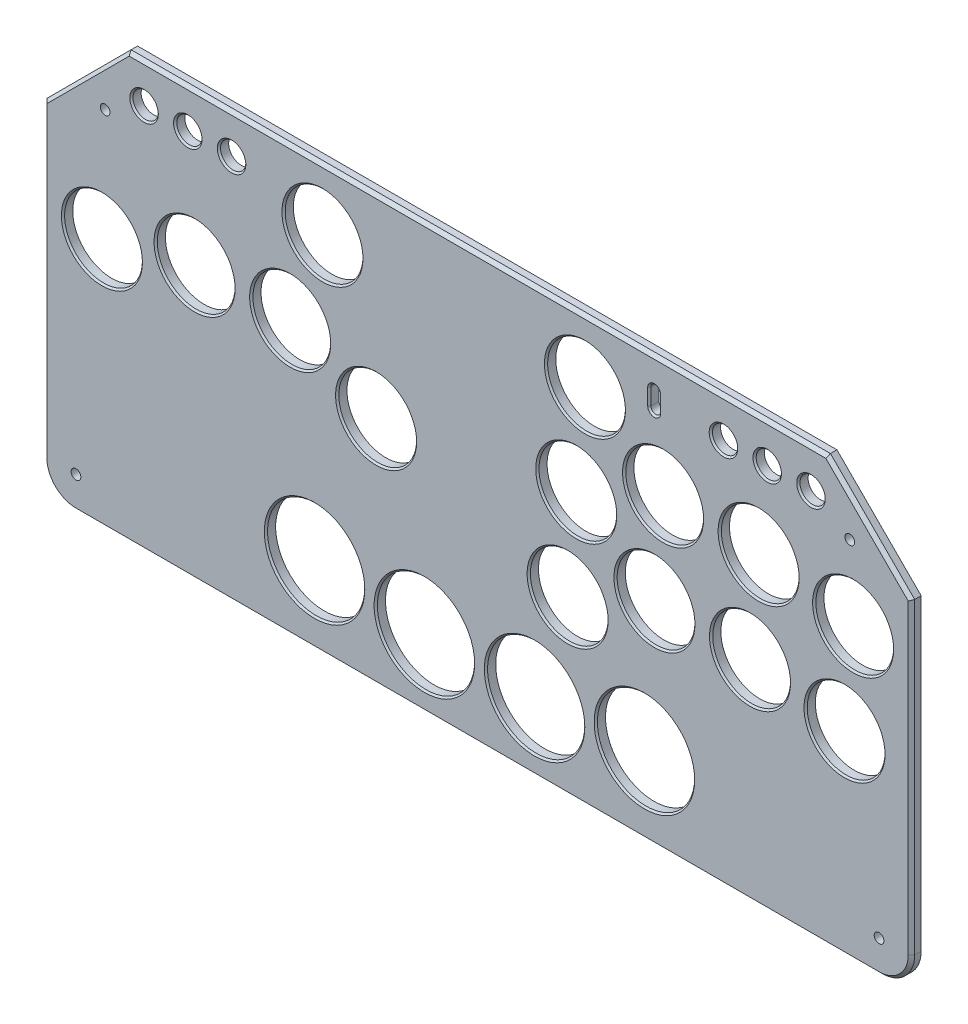
SolidWorks part; units mm, degrees
ref_plane "Front Plane" through (0, 0, 0) normal (0, 0, 1) x (1, 0, 0)
ref_plane "Top Plane" through (0, 0, 0) normal (0, 1, 0) x (1, 0, 0)
ref_plane "Right Plane" through (0, 0, 0) normal (1, 0, 0) x (0, 0, -1)
sketch "Sketch1" plane through (0, 0, 0) normal (0, 0, 1) x (1, 0, 0)
  line L0 (157.8919, 26.2701) -> (191.7747, 29.0915)
  line L1 (157.8919, 26.2701) -> (191.7747, 26.2701)
  line L2 (157.8919, 26.2701) -> (157.8919, 29.0915)
  line L3 (157.8919, 29.0915) -> (191.7747, 29.0915)
  line L4 (191.7747, 26.2701) -> (191.7747, 29.0915)
  line L5 (123.8919, 26.2701) -> (90.0092, 26.2701)
  line L6 (123.8919, 26.2701) -> (123.8919, 29.0915)
  line L7 (123.8919, 29.0915) -> (90.0092, 29.0915)
  line L8 (90.0092, 26.2701) -> (90.0092, 29.0915)
  line L9 (90.0092, 29.0915) -> (123.8919, 26.2701)
  line L10 (168.0919, 58.3601) -> (194.8735, 70.7292)
  line L11 (168.0919, 58.3601) -> (194.8735, 58.3601)
  line L12 (168.0919, 58.3601) -> (168.0919, 70.7292)
  line L13 (168.0919, 70.7292) -> (194.8735, 70.7292)
  line L14 (194.8735, 58.3601) -> (194.8735, 70.7292)
  line L15 (194.8735, 70.7292) -> (224.3587, 70.7292)
  line L16 (194.8735, 70.7292) -> (194.8735, 69.7923)
  line L17 (194.8735, 69.7923) -> (224.3587, 69.7923)
  line L18 (224.3587, 70.7292) -> (224.3587, 69.7923)
  line L19 (224.3587, 69.7923) -> (253.5106, 69.7923)
  line L20 (224.3587, 69.7923) -> (224.3587, 65.2742)
  line L21 (224.3587, 65.2742) -> (253.5106, 65.2742)
  line L22 (253.5106, 69.7923) -> (253.5106, 65.2742)
  line L23 (224.3587, 69.7923) -> (194.8735, 70.7292)
  line L24 (253.5106, 65.2742) -> (224.3587, 69.7923)
  line L25 (170.7502, 87.7401) -> (168.0919, 58.3601)
  line L26 (168.0919, 58.3601) -> (170.7502, 58.3601)
  line L27 (168.0919, 58.3601) -> (168.0919, 87.7401)
  line L28 (168.0919, 87.7401) -> (170.7502, 87.7401)
  line L29 (170.7502, 58.3601) -> (170.7502, 87.7401)
  line L30 (52.9966, 89.4705) -> (24.4119, 82.1791)
  line L31 (24.4119, 82.1791) -> (52.9966, 82.1791)
  line L32 (24.4119, 82.1791) -> (24.4119, 89.4705)
  line L33 (24.4119, 89.4705) -> (52.9966, 89.4705)
  line L34 (52.9966, 82.1791) -> (52.9966, 89.4705)
  line L35 (82.4966, 89.4705) -> (109.0019, 89.4705)
  line L36 (82.4966, 89.4705) -> (82.4966, 76.5201)
  line L37 (82.4966, 76.5201) -> (109.0019, 76.5201)
  line L38 (109.0019, 89.4705) -> (109.0019, 76.5201)
  line L39 (92.4554, 117.2387) -> (82.4966, 117.2387)
  line L40 (92.4554, 117.2387) -> (92.4554, 89.4705)
  line L41 (92.4554, 89.4705) -> (82.4966, 89.4705)
  line L42 (82.4966, 117.2387) -> (82.4966, 89.4705)
  line L43 (92.4554, 117.2387) -> (82.4966, 89.4705)
  line L44 (109.0019, 76.5201) -> (82.4966, 89.4705)
  circle A0 centre (123.8919, 26.2701) radius 14.25
  circle A1 centre (157.8919, 26.2701) radius 14.25
  circle A2 centre (90.0092, 29.0915) radius 14.25
  circle A3 centre (191.7747, 29.0915) radius 14.25
  circle A4 centre (82.4966, 89.4705) radius 11.25
  circle A5 centre (92.4554, 117.2387) radius 11.25
  circle A6 centre (52.9966, 89.4705) radius 11.25
  circle A7 centre (109.0019, 76.5201) radius 11.25
  circle A8 centre (24.4119, 82.1791) radius 11.25
  circle A9 centre (170.7502, 87.7401) radius 11.25
  circle A10 centre (168.0919, 58.3601) radius 11.25
  circle A11 centre (197.5318, 100.1092) radius 11.25
  circle A12 centre (194.8735, 70.7292) radius 11.25
  circle A13 centre (227.0169, 99.1723) radius 11.25
  circle A14 centre (224.3587, 69.7923) radius 11.25
  circle A15 centre (256.1689, 94.6541) radius 11.25
  circle A16 centre (253.5106, 65.2742) radius 11.25
  circle A17 centre (24.4119, 82.1791) radius 12
  circle A18 centre (52.9966, 89.4705) radius 12
  circle A19 centre (92.4554, 117.2387) radius 12
  circle A20 centre (82.4966, 89.4705) radius 12
  circle A21 centre (109.0019, 76.5201) radius 12
  circle A22 centre (168.0919, 58.3601) radius 12
  circle A23 centre (194.8735, 70.7292) radius 12
  circle A24 centre (224.3587, 69.7923) radius 12
  circle A25 centre (253.5106, 65.2742) radius 12
  circle A26 centre (256.1689, 94.6541) radius 12
  circle A27 centre (227.0169, 99.1723) radius 12
  circle A28 centre (197.5318, 100.1092) radius 12
  circle A29 centre (170.7502, 87.7401) radius 12
  circle A30 centre (191.7747, 29.0915) radius 15
  circle A31 centre (157.8919, 26.2701) radius 15
  circle A32 centre (123.8919, 26.2701) radius 15
  circle A33 centre (90.0092, 29.0915) radius 15
  circle A34 centre (173.429, 117.1182) radius 11.25
  circle A35 centre (173.429, 117.1182) radius 12
  dimension "D1" = 28.5
  dimension "D2" = 22.5
  dimension "D3" = 0.75
  dimension "D4" = 0.75
  dimension "D34" = 34
  dimension "D5" = 29.5
  dimension "D6" = 29.5
  dimension "D7" = 29.5
  dimension "D8" = 29.5
  dimension "D9" = 29.5
  dimension "D10" = 29.5
  dimension "D11" = 29.5
  dimension "D12" = 29.5
  dimension "D13" = 29.5
  dimension "D14" = 29.5
  dimension "D15" = 29.5
  dimension "D16" = 29.5
  dimension "D17" = 29.5
  dimension "D18" = 29.5
  dimension "D19" = 34
  dimension "D20" = 34
  dimension "D21" = 32.09
  dimension "D22" = 10.2
  dimension "D23" = 4.76
  dimension "D24" = 4.76
  dimension "D25" = 24.79
  dimension "D26" = 1.82
  dimension "D27" = 8.81
  dimension "D28" = 84.83
  dimension "D29" = 75.69
  dimension "D30" = 70.27
  dimension "D31" = 26.04
  dimension "D32" = 14.89
  dimension "D33" = 50.25
  dimension "D35" = 29.5
  dimension "D36" = 29.5
sketch "Sketch4" plane through (-30.2083, 20.075, 0) normal (0, 0, 1) x (0.9781, -0.2079, 0)
  line L0 (86.1706, 94.1917) -> (105.2206, 75.1417)
  line L1 (67.1206, 94.1917) -> (86.1706, 94.1917)
  line L2 (67.1206, 94.1917) -> (67.1206, 75.1417)
  line L3 (67.1206, 75.1417) -> (86.1706, 75.1417)
  line L4 (86.1706, 94.1917) -> (86.1706, 75.1417)
  line L5 (86.1706, 94.1917) -> (105.2206, 94.1917)
  line L6 (86.1706, 94.1917) -> (86.1706, 75.1417)
  line L7 (86.1706, 75.1417) -> (105.2206, 75.1417)
  line L8 (105.2206, 94.1917) -> (105.2206, 75.1417)
  line L9 (105.2206, 94.1917) -> (124.2706, 94.1917)
  line L10 (105.2206, 94.1917) -> (105.2206, 75.1417)
  line L11 (105.2206, 75.1417) -> (124.2706, 75.1417)
  line L12 (124.2706, 94.1917) -> (124.2706, 75.1417)
  line L13 (86.1706, 94.1917) -> (105.2206, 94.1917)
  line L14 (86.1706, 94.1917) -> (86.1706, 113.2417)
  line L15 (86.1706, 113.2417) -> (105.2206, 113.2417)
  line L16 (105.2206, 94.1917) -> (105.2206, 113.2417)
  line L17 (66.9585, 85.1784) -> (124.4326, 84.1551)
  point P14 (95.6956, 84.6667)
  point P15 (95.6956, 84.6667)
  dimension "D1" = 19.05
sketch "Sketch9" plane through (0, 0, 0) normal (0, 0, 1) x (1, 0, 0)
  line L1 (17.3619, 89.2291) -> (31.4619, 89.2291)
  line L2 (17.3619, 89.2291) -> (17.3619, 75.1291)
  line L3 (17.3619, 75.1291) -> (31.4619, 75.1291)
  line L4 (31.4619, 89.2291) -> (31.4619, 75.1291)
  line L5 (45.9466, 96.5205) -> (60.0466, 96.5205)
  line L6 (45.9466, 96.5205) -> (45.9466, 82.4205)
  line L7 (45.9466, 82.4205) -> (60.0466, 82.4205)
  line L8 (60.0466, 96.5205) -> (60.0466, 82.4205)
  line L9 (75.4466, 96.5205) -> (89.5466, 96.5205)
  line L10 (75.4466, 96.5205) -> (75.4466, 82.4205)
  line L11 (75.4466, 82.4205) -> (89.5466, 82.4205)
  line L12 (89.5466, 96.5205) -> (89.5466, 82.4205)
  line L13 (101.9519, 83.5701) -> (116.0519, 83.5701)
  line L14 (101.9519, 83.5701) -> (101.9519, 69.4701)
  line L15 (101.9519, 69.4701) -> (116.0519, 69.4701)
  line L16 (116.0519, 83.5701) -> (116.0519, 69.4701)
  line L17 (85.4054, 124.2887) -> (99.5054, 124.2887)
  line L18 (85.4054, 124.2887) -> (85.4054, 110.1887)
  line L19 (85.4054, 110.1887) -> (99.5054, 110.1887)
  line L20 (99.5054, 124.2887) -> (99.5054, 110.1887)
  line L21 (82.9592, 36.1415) -> (97.0592, 36.1415)
  line L22 (82.9592, 36.1415) -> (82.9592, 22.0415)
  line L23 (82.9592, 22.0415) -> (97.0592, 22.0415)
  line L24 (97.0592, 36.1415) -> (97.0592, 22.0415)
  line L25 (116.8419, 33.3201) -> (130.9419, 33.3201)
  line L26 (116.8419, 33.3201) -> (116.8419, 19.2201)
  line L27 (116.8419, 19.2201) -> (130.9419, 19.2201)
  line L28 (130.9419, 33.3201) -> (130.9419, 19.2201)
  line L29 (150.8419, 33.3201) -> (164.9419, 33.3201)
  line L30 (150.8419, 33.3201) -> (150.8419, 19.2201)
  line L31 (150.8419, 19.2201) -> (164.9419, 19.2201)
  line L32 (164.9419, 33.3201) -> (164.9419, 19.2201)
  line L33 (184.7247, 36.1415) -> (198.8247, 36.1415)
  line L34 (184.7247, 36.1415) -> (184.7247, 22.0415)
  line L35 (184.7247, 22.0415) -> (198.8247, 22.0415)
  line L36 (198.8247, 36.1415) -> (198.8247, 22.0415)
  line L37 (260.5606, 58.2242) -> (246.4606, 58.2242)
  line L38 (260.5606, 58.2242) -> (260.5606, 72.3242)
  line L39 (260.5606, 72.3242) -> (246.4606, 72.3242)
  line L40 (246.4606, 58.2242) -> (246.4606, 72.3242)
  line L41 (217.3087, 76.8423) -> (231.4087, 76.8423)
  line L42 (217.3087, 76.8423) -> (217.3087, 62.7423)
  line L43 (217.3087, 62.7423) -> (231.4087, 62.7423)
  line L44 (231.4087, 76.8423) -> (231.4087, 62.7423)
  line L45 (187.8235, 77.7792) -> (201.9235, 77.7792)
  line L46 (187.8235, 77.7792) -> (187.8235, 63.6792)
  line L47 (187.8235, 63.6792) -> (201.9235, 63.6792)
  line L48 (201.9235, 77.7792) -> (201.9235, 63.6792)
  line L49 (161.0419, 65.4101) -> (175.1419, 65.4101)
  line L50 (161.0419, 65.4101) -> (161.0419, 51.3101)
  line L51 (161.0419, 51.3101) -> (175.1419, 51.3101)
  line L52 (175.1419, 65.4101) -> (175.1419, 51.3101)
  line L53 (163.7002, 94.7901) -> (177.8002, 94.7901)
  line L54 (163.7002, 94.7901) -> (163.7002, 80.6901)
  line L55 (163.7002, 80.6901) -> (177.8002, 80.6901)
  line L56 (177.8002, 94.7901) -> (177.8002, 80.6901)
  line L57 (190.4818, 107.1592) -> (204.5818, 107.1592)
  line L58 (190.4818, 107.1592) -> (190.4818, 93.0592)
  line L59 (190.4818, 93.0592) -> (204.5818, 93.0592)
  line L60 (204.5818, 107.1592) -> (204.5818, 93.0592)
  line L61 (219.9669, 106.2223) -> (234.0669, 106.2223)
  line L62 (219.9669, 106.2223) -> (219.9669, 92.1223)
  line L63 (219.9669, 92.1223) -> (234.0669, 92.1223)
  line L64 (234.0669, 106.2223) -> (234.0669, 92.1223)
  line L65 (249.1189, 101.7041) -> (263.2189, 101.7041)
  line L66 (249.1189, 101.7041) -> (249.1189, 87.6041)
  line L67 (249.1189, 87.6041) -> (263.2189, 87.6041)
  line L68 (263.2189, 101.7041) -> (263.2189, 87.6041)
  line L69 (166.379, 124.1682) -> (180.479, 124.1682)
  line L70 (166.379, 124.1682) -> (166.379, 110.0682)
  line L71 (166.379, 110.0682) -> (180.479, 110.0682)
  line L72 (180.479, 124.1682) -> (180.479, 110.0682)
  point P72 (24.4119, 89.2291)
  point P74 (52.9966, 96.5205)
  point P76 (82.4966, 96.5205)
  point P78 (92.4554, 124.2887)
  point P80 (109.0019, 83.5701)
  point P82 (90.0092, 36.1415)
  point P84 (123.8919, 33.3201)
  point P86 (157.8919, 33.3201)
  point P88 (191.7747, 36.1415)
  point P90 (168.0919, 65.4101)
  point P92 (170.7502, 94.7901)
  point P94 (173.429, 124.1682)
  point P96 (197.5318, 107.1592)
  point P98 (227.0169, 106.2223)
  point P100 (256.1689, 101.7041)
  point P102 (194.8735, 77.7792)
  point P104 (224.3587, 76.8423)
  point P106 (253.5106, 72.3242)
  point P108 (17.3619, 82.1791)
  point P109 (45.9466, 89.4705)
  point P110 (75.4466, 89.4705)
  point P111 (101.9519, 76.5201)
  point P112 (85.4054, 117.2387)
  point P113 (82.9592, 29.0915)
  point P114 (116.8419, 26.2701)
  point P115 (150.8419, 26.2701)
  point P116 (184.7247, 29.0915)
  point P118 (161.0419, 58.3601)
  point P119 (187.8235, 70.7292)
  point P120 (217.3087, 69.7923)
  point P121 (246.4606, 65.2742)
  point P122 (163.7002, 87.7401)
  point P123 (190.4818, 100.1092)
  point P124 (219.9669, 99.1723)
  point P125 (249.1189, 94.6541)
  point P126 (166.379, 117.1182)
  dimension "D1" = 14.1
sketch "Sketch10" plane through (-22.0981, 19.3454, 0) normal (0, 0, 1) x (0.9781, -0.2079, 0)
  line L1 (61.5108, 90.7441) -> (75.6108, 90.7441)
  line L2 (61.5108, 90.7441) -> (61.5108, 76.6441)
  line L3 (61.5108, 76.6441) -> (75.6108, 76.6441)
  line L4 (75.6108, 90.7441) -> (75.6108, 76.6441)
  line L5 (80.5608, 90.7441) -> (94.6608, 90.7441)
  line L6 (80.5608, 90.7441) -> (80.5608, 76.6441)
  line L7 (80.5608, 76.6441) -> (94.6608, 76.6441)
  line L8 (94.6608, 90.7441) -> (94.6608, 76.6441)
  line L9 (99.6108, 90.7441) -> (113.7108, 90.7441)
  line L10 (99.6108, 90.7441) -> (99.6108, 76.6441)
  line L11 (99.6108, 76.6441) -> (113.7108, 76.6441)
  line L12 (113.7108, 90.7441) -> (113.7108, 76.6441)
  line L13 (80.5608, 109.7941) -> (94.6608, 109.7941)
  line L14 (80.5608, 109.7941) -> (80.5608, 95.6941)
  line L15 (80.5608, 95.6941) -> (94.6608, 95.6941)
  line L16 (94.6608, 109.7941) -> (94.6608, 95.6941)
  line L17 (50.5121, 89.6359) -> (53.4436, 75.8441) construction
  line L18 (59.0358, 93.2191) -> (78.0858, 93.2191) construction
  line L19 (78.0858, 112.2691) -> (97.1358, 112.2691) construction
  line L20 (97.1358, 93.2191) -> (116.1858, 93.2191) construction
  line L21 (78.0858, 93.2191) -> (78.0858, 112.2691) construction
  line L23 (59.0358, 93.2191) -> (59.0358, 74.1691) construction
  point P16 (75.6108, 83.6941)
  point P17 (94.6608, 83.6941)
  point P18 (113.7108, 83.6941)
  point P19 (87.6108, 90.7441)
  point P20 (87.6108, 109.7941)
  point P23 (68.5608, 90.7441)
  point P26 (68.5608, 93.2191)
  point P29 (87.6108, 112.2691)
  point P30 (106.6608, 90.7441)
  point P33 (106.6608, 93.2191)
  point P34 (80.5608, 102.7441)
  point P37 (78.0858, 102.7441)
  point P42 (59.0358, 83.6941)
  point P43 (61.5108, 83.6941)
sketch "Sketch14" plane through (0, 0, 0) normal (0, 0, 1) x (1, 0, 0)
  line L0 (165.1144, 80.6901) -> (163.7002, 82.1043)
  line L1 (163.7002, 93.3758) -> (165.1144, 94.7901)
  line L2 (177.8002, 93.3758) -> (176.386, 94.7901)
  line L3 (179.0648, 110.0682) -> (180.479, 111.4824)
  line L4 (166.379, 111.4824) -> (167.7932, 110.0682)
  line L5 (166.379, 122.754) -> (167.7932, 124.1682)
  line L6 (179.0648, 124.1682) -> (180.479, 122.754)
  line L7 (203.1676, 93.0592) -> (204.5818, 94.4734)
  line L8 (17.3619, 89.2291) -> (17.3619, 75.1291) construction
  line L9 (17.3619, 89.2291) -> (31.4619, 89.2291) construction
  line L10 (17.3619, 87.8149) -> (18.7761, 89.2291)
  line L11 (17.3619, 75.1291) -> (31.4619, 75.1291) construction
  line L12 (31.4619, 89.2291) -> (31.4619, 75.1291) construction
  line L13 (45.9466, 96.5205) -> (60.0466, 96.5205) construction
  line L14 (60.0466, 96.5205) -> (60.0466, 82.4205) construction
  line L15 (45.9466, 96.5205) -> (45.9466, 82.4205) construction
  line L16 (45.9466, 82.4205) -> (60.0466, 82.4205) construction
  line L17 (85.4054, 124.2887) -> (85.4054, 110.1887) construction
  line L18 (85.4054, 124.2887) -> (99.5054, 124.2887) construction
  line L19 (99.5054, 124.2887) -> (99.5054, 110.1887) construction
  line L20 (85.4054, 110.1887) -> (99.5054, 110.1887) construction
  line L21 (101.9519, 83.5701) -> (101.9519, 69.4701) construction
  line L22 (101.9519, 83.5701) -> (116.0519, 83.5701) construction
  line L23 (116.0519, 83.5701) -> (116.0519, 69.4701) construction
  line L24 (101.9519, 69.4701) -> (116.0519, 69.4701) construction
  line L25 (91.2712, 73.6044) -> (105.0631, 70.6729) construction
  line L26 (107.9947, 84.4647) -> (105.0631, 70.6729) construction
  line L27 (94.2028, 87.3963) -> (107.9947, 84.4647) construction
  line L28 (94.2028, 87.3963) -> (91.2712, 73.6044) construction
  line L29 (72.6375, 77.5651) -> (86.4294, 74.6336) construction
  line L30 (89.361, 88.4255) -> (86.4294, 74.6336) construction
  line L31 (75.5691, 91.357) -> (89.361, 88.4255) construction
  line L32 (75.5691, 91.357) -> (72.6375, 77.5651) construction
  line L33 (56.9354, 95.3177) -> (54.0038, 81.5259) construction
  line L34 (56.9354, 95.3177) -> (70.7273, 92.3862) construction
  line L35 (70.7273, 92.3862) -> (67.7957, 78.5943) construction
  line L36 (54.0038, 81.5259) -> (67.7957, 78.5943) construction
  line L37 (76.5983, 96.1988) -> (90.3901, 93.2673) construction
  line L38 (93.3217, 107.0592) -> (90.3901, 93.2673) construction
  line L39 (79.5298, 109.9907) -> (76.5983, 96.1988) construction
  line L40 (79.5298, 109.9907) -> (93.3217, 107.0592) construction
  line L41 (82.9592, 36.1415) -> (82.9592, 22.0415) construction
  line L42 (82.9592, 36.1415) -> (97.0592, 36.1415) construction
  line L43 (82.9592, 22.0415) -> (97.0592, 22.0415) construction
  line L44 (97.0592, 36.1415) -> (97.0592, 22.0415) construction
  line L45 (116.8419, 33.3201) -> (116.8419, 19.2201) construction
  line L46 (116.8419, 33.3201) -> (130.9419, 33.3201) construction
  line L47 (116.8419, 19.2201) -> (130.9419, 19.2201) construction
  line L48 (130.9419, 33.3201) -> (130.9419, 19.2201) construction
  line L49 (150.8419, 33.3201) -> (150.8419, 19.2201) construction
  line L50 (150.8419, 33.3201) -> (164.9419, 33.3201) construction
  line L51 (164.9419, 33.3201) -> (164.9419, 19.2201) construction
  line L52 (150.8419, 19.2201) -> (164.9419, 19.2201) construction
  line L53 (184.7247, 36.1415) -> (184.7247, 22.0415) construction
  line L54 (184.7247, 22.0415) -> (198.8247, 22.0415) construction
  line L55 (198.8247, 36.1415) -> (198.8247, 22.0415) construction
  line L56 (184.7247, 36.1415) -> (198.8247, 36.1415) construction
  line L57 (161.0419, 65.4101) -> (175.1419, 65.4101) construction
  line L58 (175.1419, 65.4101) -> (175.1419, 51.3101) construction
  line L59 (161.0419, 51.3101) -> (175.1419, 51.3101) construction
  line L60 (161.0419, 65.4101) -> (161.0419, 51.3101) construction
  line L61 (187.8235, 77.7792) -> (187.8235, 63.6792) construction
  line L62 (187.8235, 77.7792) -> (201.9235, 77.7792) construction
  line L63 (187.8235, 63.6792) -> (201.9235, 63.6792) construction
  line L64 (201.9235, 77.7792) -> (201.9235, 63.6792) construction
  line L65 (217.3087, 76.8423) -> (217.3087, 62.7423) construction
  line L66 (217.3087, 76.8423) -> (231.4087, 76.8423) construction
  line L67 (231.4087, 76.8423) -> (231.4087, 62.7423) construction
  line L68 (217.3087, 62.7423) -> (231.4087, 62.7423) construction
  line L69 (260.5606, 58.2242) -> (246.4606, 58.2242) construction
  line L70 (260.5606, 58.2242) -> (260.5606, 72.3242) construction
  line L71 (246.4606, 58.2242) -> (246.4606, 72.3242) construction
  line L72 (260.5606, 72.3242) -> (246.4606, 72.3242) construction
  line L73 (249.1189, 101.7041) -> (263.2189, 101.7041) construction
  line L74 (263.2189, 101.7041) -> (263.2189, 87.6041) construction
  line L75 (249.1189, 87.6041) -> (263.2189, 87.6041) construction
  line L76 (249.1189, 101.7041) -> (249.1189, 87.6041) construction
  line L77 (219.9669, 106.2223) -> (219.9669, 92.1223) construction
  line L78 (219.9669, 106.2223) -> (234.0669, 106.2223) construction
  line L79 (234.0669, 106.2223) -> (234.0669, 92.1223) construction
  line L80 (219.9669, 92.1223) -> (234.0669, 92.1223) construction
  line L81 (190.4818, 107.1592) -> (204.5818, 107.1592) construction
  line L82 (204.5818, 107.1592) -> (204.5818, 93.0592) construction
  line L83 (190.4818, 93.0592) -> (204.5818, 93.0592) construction
  line L84 (190.4818, 107.1592) -> (190.4818, 93.0592) construction
  line L85 (163.7002, 94.7901) -> (177.8002, 94.7901) construction
  line L86 (177.8002, 94.7901) -> (177.8002, 80.6901) construction
  line L87 (163.7002, 80.6901) -> (177.8002, 80.6901) construction
  line L88 (163.7002, 94.7901) -> (163.7002, 80.6901) construction
  line L89 (180.479, 124.1682) -> (180.479, 110.0682) construction
  line L90 (166.379, 110.0682) -> (180.479, 110.0682) construction
  line L91 (166.379, 124.1682) -> (166.379, 110.0682) construction
  line L92 (166.379, 124.1682) -> (180.479, 124.1682) construction
  line L93 (17.3619, 76.5433) -> (18.7761, 75.1291)
  line L94 (30.0477, 75.1291) -> (31.4619, 76.5433)
  line L95 (31.4619, 87.8149) -> (30.0477, 89.2291)
  line L96 (45.9466, 95.1063) -> (47.3608, 96.5205)
  line L97 (45.9466, 83.8347) -> (47.3608, 82.4205)
  line L98 (54.2979, 82.9092) -> (55.3871, 81.2318)
  line L99 (58.6323, 82.4205) -> (60.0466, 83.8347)
  line L100 (56.6413, 93.9344) -> (58.3187, 95.0237)
  line L101 (58.6323, 96.5205) -> (60.0466, 95.1063)
  line L102 (69.3439, 92.6802) -> (70.4332, 91.0029)
  line L103 (68.0897, 79.9776) -> (66.4124, 78.8883)
  line L104 (75.2751, 89.9737) -> (76.9524, 91.063)
  line L105 (72.9316, 78.9484) -> (74.0208, 77.2711)
  line L106 (85.0461, 74.9276) -> (86.7234, 76.0169)
  line L107 (89.0669, 87.0421) -> (87.9777, 88.7195)
  line L108 (89.0068, 93.5613) -> (90.6842, 94.6506)
  line L109 (76.8923, 97.5822) -> (77.9816, 95.9048)
  line L110 (91.9384, 107.3532) -> (93.0277, 105.6759)
  line L111 (79.2358, 108.6074) -> (80.9131, 109.6967)
  line L112 (85.4054, 111.6029) -> (86.8196, 110.1887)
  line L113 (98.0912, 110.1887) -> (99.5054, 111.6029)
  line L114 (98.0912, 124.2887) -> (99.5054, 122.8745)
  line L115 (85.4054, 122.8745) -> (86.8196, 124.2887)
  line L116 (93.9088, 86.013) -> (95.5861, 87.1023)
  line L117 (91.5653, 74.9877) -> (92.6546, 73.3104)
  line L118 (103.6798, 70.9669) -> (105.3572, 72.0562)
  line L119 (106.6114, 84.7588) -> (107.7006, 83.0814)
  line L120 (101.9519, 82.1559) -> (103.3662, 83.5701)
  line L121 (101.9519, 70.8843) -> (103.3662, 69.4701)
  line L122 (114.6377, 69.4701) -> (116.0519, 70.8843)
  line L123 (116.0519, 82.1559) -> (114.6377, 83.5701)
  line L124 (82.9592, 34.7272) -> (84.3734, 36.1415)
  line L125 (82.9592, 23.4557) -> (84.3734, 22.0415)
  line L126 (95.645, 22.0415) -> (97.0592, 23.4557)
  line L127 (97.0592, 34.7272) -> (95.645, 36.1415)
  line L128 (116.8419, 31.9059) -> (118.2562, 33.3201)
  line L129 (116.8419, 20.6343) -> (118.2562, 19.2201)
  line L130 (129.5277, 19.2201) -> (130.9419, 20.6343)
  line L131 (130.9419, 31.9059) -> (129.5277, 33.3201)
  line L132 (150.8419, 31.9059) -> (152.2562, 33.3201)
  line L133 (150.8419, 20.6343) -> (152.2562, 19.2201)
  line L134 (163.5277, 19.2201) -> (164.9419, 20.6343)
  line L135 (164.9419, 31.9059) -> (163.5277, 33.3201)
  line L136 (184.7247, 34.7272) -> (186.1389, 36.1415)
  line L137 (184.7247, 23.4557) -> (186.1389, 22.0415)
  line L138 (197.4105, 22.0415) -> (198.8247, 23.4557)
  line L139 (198.8247, 34.7272) -> (197.4105, 36.1415)
  line L140 (173.7277, 51.3101) -> (175.1419, 52.7243)
  line L141 (161.0419, 52.7243) -> (162.4562, 51.3101)
  line L142 (161.0419, 63.9959) -> (162.4562, 65.4101)
  line L143 (173.7277, 65.4101) -> (175.1419, 63.9959)
  line L144 (187.8235, 65.0934) -> (189.2378, 63.6792)
  line L145 (200.5093, 63.6792) -> (201.9235, 65.0934)
  line L146 (200.5093, 77.7792) -> (201.9235, 76.365)
  line L147 (187.8235, 76.365) -> (189.2378, 77.7792)
  line L148 (176.386, 80.6901) -> (177.8002, 82.1043)
  line L149 (204.5818, 105.745) -> (203.1676, 107.1592)
  line L150 (191.896, 107.1592) -> (190.4818, 105.745)
  line L151 (190.4818, 94.4734) -> (191.896, 93.0592)
  line L152 (219.9669, 104.8081) -> (221.3812, 106.2223)
  line L153 (232.6527, 106.2223) -> (234.0669, 104.8081)
  line L154 (234.0669, 93.5365) -> (232.6527, 92.1223)
  line L155 (219.9669, 93.5365) -> (221.3812, 92.1223)
  line L156 (229.9944, 76.8423) -> (231.4087, 75.4281)
  line L157 (217.3087, 75.4281) -> (218.7229, 76.8423)
  line L158 (217.3087, 64.1565) -> (218.7229, 62.7423)
  line L159 (229.9944, 62.7423) -> (231.4087, 64.1565)
  line L160 (259.1464, 72.3242) -> (260.5606, 70.9099)
  line L161 (246.4606, 70.9099) -> (247.8748, 72.3242)
  line L162 (259.1464, 58.2242) -> (260.5606, 59.6384)
  line L163 (247.8748, 58.2242) -> (246.4606, 59.6384)
  line L164 (261.8047, 87.6041) -> (263.2189, 89.0183)
  line L165 (249.1189, 89.0183) -> (250.5331, 87.6041)
  line L166 (249.1189, 100.2899) -> (250.5331, 101.7041)
  line L167 (261.8047, 101.7041) -> (263.2189, 100.2899)
  line L168 (75.4466, 96.5205) -> (75.4466, 82.4205) construction
  line L169 (75.4466, 96.5205) -> (89.5466, 96.5205) construction
  line L170 (89.5466, 96.5205) -> (89.5466, 82.4205) construction
  line L171 (75.4466, 82.4205) -> (89.5466, 82.4205) construction
  line L172 (76.8608, 96.5205) -> (75.4466, 95.1063)
  line L173 (88.1323, 96.5205) -> (89.5466, 95.1063)
  line L174 (89.5466, 83.8347) -> (88.1323, 82.4205)
  line L175 (75.4466, 83.8347) -> (76.8608, 82.4205)
  arc A0 (17.3619, 87.8149) -> (18.7761, 89.2291) centre (18.069, 88.522) cw
  arc A1 (18.7761, 75.1291) -> (17.3619, 76.5433) centre (18.069, 75.8362) cw
  arc A2 (31.4619, 76.5433) -> (30.0477, 75.1291) centre (30.7548, 75.8362) cw
  arc A3 (30.0477, 89.2291) -> (31.4619, 87.8149) centre (30.7548, 88.522) cw
  arc A4 (58.6323, 96.5205) -> (60.0466, 95.1063) centre (59.3394, 95.8134) cw
  arc A5 (45.9466, 95.1063) -> (47.3608, 96.5205) centre (46.6537, 95.8134) cw
  arc A6 (47.3608, 82.4205) -> (45.9466, 83.8347) centre (46.6537, 83.1276) cw
  arc A7 (60.0466, 83.8347) -> (58.6323, 82.4205) centre (59.3394, 83.1276) cw
  arc A8 (85.4054, 122.8745) -> (86.8196, 124.2887) centre (86.1125, 123.5816) cw
  arc A9 (98.0912, 124.2887) -> (99.5054, 122.8745) centre (98.7983, 123.5816) cw
  arc A10 (99.5054, 111.6029) -> (98.0912, 110.1887) centre (98.7983, 110.8958) cw
  arc A11 (85.4054, 111.6029) -> (86.8196, 110.1887) centre (86.1125, 110.8958) ccw
  arc A12 (101.9519, 82.1559) -> (103.3662, 83.5701) centre (102.6591, 82.863) cw
  arc A13 (114.6377, 83.5701) -> (116.0519, 82.1559) centre (115.3448, 82.863) cw
  arc A14 (116.0519, 70.8843) -> (114.6377, 69.4701) centre (115.3448, 70.1772) cw
  arc A15 (101.9519, 70.8843) -> (103.3662, 69.4701) centre (102.6591, 70.1772) ccw
  arc A16 (103.6798, 70.9669) -> (105.3572, 72.0562) centre (104.5185, 71.5115) ccw
  arc A17 (106.6114, 84.7588) -> (107.7006, 83.0814) centre (107.156, 83.9201) cw
  arc A18 (93.9088, 86.013) -> (95.5861, 87.1023) centre (94.7474, 86.5576) cw
  arc A19 (91.5653, 74.9877) -> (92.6546, 73.3104) centre (92.1099, 74.1491) ccw
  arc A20 (85.0461, 74.9276) -> (86.7234, 76.0169) centre (85.8848, 75.4722) ccw
  arc A21 (87.9777, 88.7195) -> (89.0669, 87.0421) centre (88.5223, 87.8808) cw
  arc A22 (75.2751, 89.9737) -> (76.9524, 91.063) centre (76.1137, 90.5183) cw
  arc A23 (72.9316, 78.9484) -> (74.0208, 77.2711) centre (73.4762, 78.1098) ccw
  arc A24 (56.6413, 93.9344) -> (58.3187, 95.0237) centre (57.48, 94.4791) cw
  arc A25 (69.3439, 92.6802) -> (70.4332, 91.0029) centre (69.8886, 91.8415) cw
  arc A26 (68.0897, 79.9776) -> (66.4124, 78.8883) centre (67.2511, 79.433) cw
  arc A27 (54.2979, 82.9092) -> (55.3871, 81.2318) centre (54.8425, 82.0705) ccw
  arc A28 (89.0068, 93.5613) -> (90.6842, 94.6506) centre (89.8455, 94.106) ccw
  arc A29 (76.8923, 97.5822) -> (77.9816, 95.9048) centre (77.4369, 96.7435) ccw
  arc A30 (79.2358, 108.6074) -> (80.9131, 109.6967) centre (80.0744, 109.1521) cw
  arc A31 (91.9384, 107.3532) -> (93.0277, 105.6759) centre (92.483, 106.5145) cw
  arc A32 (82.9592, 34.7272) -> (84.3734, 36.1415) centre (83.6663, 35.4344) cw
  arc A33 (82.9592, 23.4557) -> (84.3734, 22.0415) centre (83.6663, 22.7486) ccw
  arc A34 (95.645, 22.0415) -> (97.0592, 23.4557) centre (96.3521, 22.7486) ccw
  arc A35 (95.645, 36.1415) -> (97.0592, 34.7272) centre (96.3521, 35.4344) cw
  arc A36 (116.8419, 31.9059) -> (118.2562, 33.3201) centre (117.5491, 32.613) cw
  arc A37 (116.8419, 20.6343) -> (118.2562, 19.2201) centre (117.5491, 19.9272) ccw
  arc A38 (129.5277, 19.2201) -> (130.9419, 20.6343) centre (130.2348, 19.9272) ccw
  arc A39 (129.5277, 33.3201) -> (130.9419, 31.9059) centre (130.2348, 32.613) cw
  arc A40 (150.8419, 31.9059) -> (152.2562, 33.3201) centre (151.5491, 32.613) cw
  arc A41 (163.5277, 33.3201) -> (164.9419, 31.9059) centre (164.2348, 32.613) cw
  arc A42 (164.9419, 20.6343) -> (163.5277, 19.2201) centre (164.2348, 19.9272) cw
  arc A43 (150.8419, 20.6343) -> (152.2562, 19.2201) centre (151.5491, 19.9272) ccw
  arc A44 (184.7247, 23.4557) -> (186.1389, 22.0415) centre (185.4318, 22.7486) ccw
  arc A45 (197.4105, 22.0415) -> (198.8247, 23.4557) centre (198.1176, 22.7486) ccw
  arc A46 (197.4105, 36.1415) -> (198.8247, 34.7272) centre (198.1176, 35.4344) cw
  arc A47 (184.7247, 34.7272) -> (186.1389, 36.1415) centre (185.4318, 35.4344) cw
  arc A48 (173.7277, 65.4101) -> (175.1419, 63.9959) centre (174.4348, 64.703) cw
  arc A49 (175.1419, 52.7243) -> (173.7277, 51.3101) centre (174.4348, 52.0172) cw
  arc A50 (161.0419, 52.7243) -> (162.4562, 51.3101) centre (161.7491, 52.0172) ccw
  arc A51 (161.0419, 63.9959) -> (162.4562, 65.4101) centre (161.7491, 64.703) cw
  arc A52 (187.8235, 76.365) -> (189.2378, 77.7792) centre (188.5306, 77.0721) cw
  arc A53 (187.8235, 65.0934) -> (189.2378, 63.6792) centre (188.5306, 64.3863) ccw
  arc A54 (200.5093, 63.6792) -> (201.9235, 65.0934) centre (201.2164, 64.3863) ccw
  arc A55 (200.5093, 77.7792) -> (201.9235, 76.365) centre (201.2164, 77.0721) cw
  arc A56 (217.3087, 75.4281) -> (218.7229, 76.8423) centre (218.0158, 76.1352) cw
  arc A57 (229.9944, 76.8423) -> (231.4087, 75.4281) centre (230.7016, 76.1352) cw
  arc A58 (231.4087, 64.1565) -> (229.9944, 62.7423) centre (230.7016, 63.4494) cw
  arc A59 (217.3087, 64.1565) -> (218.7229, 62.7423) centre (218.0158, 63.4494) ccw
  arc A60 (259.1464, 58.2242) -> (260.5606, 59.6384) centre (259.8535, 58.9313) ccw
  arc A61 (246.4606, 59.6384) -> (247.8748, 58.2242) centre (247.1677, 58.9313) ccw
  arc A62 (246.4606, 70.9099) -> (247.8748, 72.3242) centre (247.1677, 71.617) cw
  arc A63 (259.1464, 72.3242) -> (260.5606, 70.9099) centre (259.8535, 71.617) cw
  arc A64 (261.8047, 101.7041) -> (263.2189, 100.2899) centre (262.5118, 100.997) cw
  arc A65 (263.2189, 89.0183) -> (261.8047, 87.6041) centre (262.5118, 88.3112) cw
  arc A66 (250.5331, 87.6041) -> (249.1189, 89.0183) centre (249.826, 88.3112) cw
  arc A67 (249.1189, 100.2899) -> (250.5331, 101.7041) centre (249.826, 100.997) cw
  arc A68 (219.9669, 104.8081) -> (221.3812, 106.2223) centre (220.674, 105.5152) cw
  arc A69 (232.6527, 106.2223) -> (234.0669, 104.8081) centre (233.3598, 105.5152) cw
  arc A70 (234.0669, 93.5365) -> (232.6527, 92.1223) centre (233.3598, 92.8294) cw
  arc A71 (221.3812, 92.1223) -> (219.9669, 93.5365) centre (220.674, 92.8294) cw
  arc A72 (203.1676, 107.1592) -> (204.5818, 105.745) centre (203.8747, 106.4521) cw
  arc A73 (204.5818, 94.4734) -> (203.1676, 93.0592) centre (203.8747, 93.7663) cw
  arc A74 (191.896, 93.0592) -> (190.4818, 94.4734) centre (191.1889, 93.7663) cw
  arc A75 (190.4818, 105.745) -> (191.896, 107.1592) centre (191.1889, 106.4521) cw
  arc A76 (176.386, 94.7901) -> (177.8002, 93.3758) centre (177.0931, 94.0829) cw
  arc A77 (177.8002, 82.1043) -> (176.386, 80.6901) centre (177.0931, 81.3972) cw
  arc A78 (165.1144, 80.6901) -> (163.7002, 82.1043) centre (164.4073, 81.3972) cw
  arc A79 (163.7002, 93.3758) -> (165.1144, 94.7901) centre (164.4073, 94.0829) cw
  arc A80 (180.479, 111.4824) -> (179.0648, 110.0682) centre (179.7719, 110.7753) cw
  arc A81 (167.7932, 110.0682) -> (166.379, 111.4824) centre (167.0861, 110.7753) cw
  arc A82 (179.0648, 124.1682) -> (180.479, 122.754) centre (179.7719, 123.4611) cw
  arc A83 (166.379, 122.754) -> (167.7932, 124.1682) centre (167.0861, 123.4611) cw
  arc A84 (75.4466, 95.1063) -> (76.8608, 96.5205) centre (76.1537, 95.8134) cw
  arc A85 (88.1323, 96.5205) -> (89.5466, 95.1063) centre (88.8394, 95.8134) cw
  arc A86 (89.5466, 83.8347) -> (88.1323, 82.4205) centre (88.8394, 83.1276) cw
  arc A87 (76.8608, 82.4205) -> (75.4466, 83.8347) centre (76.1537, 83.1276) cw
  dimension "D1" = 45
  dimension "D2" = 1
  dimension "D71" = 45
  dimension "D3" = 45
  dimension "D4" = 45
  dimension "D5" = 45
  dimension "D6" = 45
  dimension "D7" = 45
  dimension "D8" = 45
  dimension "D9" = 45
  dimension "D10" = 45
  dimension "D11" = 45
  dimension "D12" = 45
  dimension "D13" = 45
  dimension "D14" = 45
  dimension "D15" = 45
  dimension "D16" = 45
  dimension "D17" = 45
  dimension "D18" = 45
  dimension "D19" = 45
  dimension "D20" = 45
  dimension "D21" = 45
  dimension "D22" = 45
  dimension "D23" = 45
  dimension "D24" = 45
  dimension "D25" = 45
  dimension "D26" = 45
  dimension "D27" = 45
  dimension "D28" = 45
  dimension "D29" = 45
  dimension "D30" = 45
  dimension "D31" = 45
  dimension "D32" = 45
  dimension "D33" = 45
  dimension "D34" = 45
  dimension "D35" = 45
  dimension "D36" = 45
  dimension "D37" = 45
  dimension "D38" = 45
  dimension "D39" = 45
  dimension "D40" = 45
  dimension "D41" = 45
  dimension "D42" = 45
  dimension "D43" = 45
  dimension "D44" = 45
  dimension "D45" = 45
  dimension "D46" = 45
  dimension "D47" = 45
  dimension "D48" = 45
  dimension "D49" = 45
  dimension "D50" = 45
  dimension "D51" = 45
  dimension "D52" = 45
  dimension "D53" = 45
  dimension "D54" = 45
  dimension "D55" = 45
  dimension "D56" = 45
  dimension "D57" = 45
  dimension "D58" = 45
  dimension "D59" = 45
  dimension "D60" = 45
  dimension "D61" = 45
  dimension "D62" = 45
  dimension "D63" = 45
  dimension "D64" = 45
  dimension "D65" = 45
  dimension "D66" = 45
  dimension "D67" = 45
  dimension "D68" = 45
  dimension "D69" = 45
  dimension "D70" = 45
  dimension "D72" = 45
  dimension "D73" = 45
  dimension "D74" = 45
  dimension "D75" = 45
  dimension "D76" = 45
  dimension "D77" = 45
  dimension "D78" = 45
  dimension "D79" = 45
  dimension "D80" = 45
  dimension "D81" = 45
  dimension "D82" = 45
  dimension "D83" = 45
  dimension "D84" = 45
  dimension "D85" = 45
  dimension "D86" = 45
  dimension "D87" = 45
  dimension "D88" = 45
  dimension "D89" = 45
sketch "Sketch16" plane through (0, 0, 0) normal (0, 0, 1) x (1, 0, 0)
  line L0 (81.0092, 30.6915) -> (99.0092, 30.6915)
  line L5 (17.3619, 89.2291) -> (17.3619, 75.1291) construction
  line L6 (81.0092, 30.6915) -> (81.0092, 27.4915)
  line L7 (17.3619, 75.1291) -> (31.4619, 75.1291) construction
  line L8 (15.4119, 83.7791) -> (33.4119, 83.7791)
  line L9 (15.4119, 83.7791) -> (15.4119, 80.5791)
  line L10 (15.4119, 80.5791) -> (33.4119, 80.5791)
  line L11 (33.4119, 83.7791) -> (33.4119, 80.5791)
  line L12 (81.0092, 27.4915) -> (99.0092, 27.4915)
  line L13 (99.0092, 30.6915) -> (99.0092, 27.4915)
  line L14 (114.8919, 27.8701) -> (132.8919, 27.8701)
  line L15 (114.8919, 27.8701) -> (114.8919, 24.6701)
  line L16 (114.8919, 24.6701) -> (132.8919, 24.6701)
  line L17 (132.8919, 27.8701) -> (132.8919, 24.6701)
  line L18 (148.8919, 27.8701) -> (166.8919, 27.8701)
  line L19 (148.8919, 27.8701) -> (148.8919, 24.6701)
  line L20 (148.8919, 24.6701) -> (166.8919, 24.6701)
  line L21 (166.8919, 27.8701) -> (166.8919, 24.6701)
  line L22 (182.7747, 30.6915) -> (200.7747, 30.6915)
  line L23 (182.7747, 30.6915) -> (182.7747, 27.4915)
  line L24 (182.7747, 27.4915) -> (200.7747, 27.4915)
  line L25 (200.7747, 30.6915) -> (200.7747, 27.4915)
  line L26 (43.9966, 91.0705) -> (61.9966, 91.0705)
  line L27 (43.9966, 91.0705) -> (43.9966, 87.8705)
  line L28 (43.9966, 87.8705) -> (61.9966, 87.8705)
  line L29 (61.9966, 91.0705) -> (61.9966, 87.8705)
  line L30 (73.4966, 91.0705) -> (91.4966, 91.0705)
  line L31 (73.4966, 91.0705) -> (73.4966, 87.8705)
  line L32 (73.4966, 87.8705) -> (91.4966, 87.8705)
  line L33 (91.4966, 91.0705) -> (91.4966, 87.8705)
  line L34 (100.0019, 78.1201) -> (118.0019, 78.1201)
  line L35 (100.0019, 78.1201) -> (100.0019, 74.9201)
  line L36 (100.0019, 74.9201) -> (118.0019, 74.9201)
  line L37 (118.0019, 78.1201) -> (118.0019, 74.9201)
  line L38 (83.4554, 118.8387) -> (101.4554, 118.8387)
  line L39 (83.4554, 118.8387) -> (83.4554, 115.6387)
  line L40 (83.4554, 115.6387) -> (101.4554, 115.6387)
  line L41 (101.4554, 118.8387) -> (101.4554, 115.6387)
  line L42 (164.429, 118.7182) -> (182.429, 118.7182)
  line L43 (164.429, 118.7182) -> (164.429, 115.5182)
  line L44 (164.429, 115.5182) -> (182.429, 115.5182)
  line L45 (182.429, 118.7182) -> (182.429, 115.5182)
  line L46 (161.7502, 89.3401) -> (179.7502, 89.3401)
  line L47 (161.7502, 89.3401) -> (161.7502, 86.1401)
  line L48 (161.7502, 86.1401) -> (179.7502, 86.1401)
  line L49 (179.7502, 89.3401) -> (179.7502, 86.1401)
  line L50 (188.5318, 101.7092) -> (206.5318, 101.7092)
  line L51 (188.5318, 101.7092) -> (188.5318, 98.5092)
  line L52 (188.5318, 98.5092) -> (206.5318, 98.5092)
  line L53 (206.5318, 101.7092) -> (206.5318, 98.5092)
  line L54 (159.0919, 59.9601) -> (177.0919, 59.9601)
  line L55 (159.0919, 59.9601) -> (159.0919, 56.7601)
  line L56 (159.0919, 56.7601) -> (177.0919, 56.7601)
  line L57 (177.0919, 59.9601) -> (177.0919, 56.7601)
  line L58 (185.8735, 72.3292) -> (203.8735, 72.3292)
  line L59 (185.8735, 72.3292) -> (185.8735, 69.1292)
  line L60 (185.8735, 69.1292) -> (203.8735, 69.1292)
  line L61 (203.8735, 72.3292) -> (203.8735, 69.1292)
  line L62 (218.0169, 100.7723) -> (236.0169, 100.7723)
  line L63 (218.0169, 100.7723) -> (218.0169, 97.5723)
  line L64 (218.0169, 97.5723) -> (236.0169, 97.5723)
  line L65 (236.0169, 100.7723) -> (236.0169, 97.5723)
  line L66 (215.3587, 71.3923) -> (233.3587, 71.3923)
  line L67 (215.3587, 71.3923) -> (215.3587, 68.1923)
  line L68 (215.3587, 68.1923) -> (233.3587, 68.1923)
  line L69 (233.3587, 71.3923) -> (233.3587, 68.1923)
  line L70 (247.1689, 96.2541) -> (265.1689, 96.2541)
  line L71 (247.1689, 96.2541) -> (247.1689, 93.0541)
  line L72 (247.1689, 93.0541) -> (265.1689, 93.0541)
  line L73 (265.1689, 96.2541) -> (265.1689, 93.0541)
  line L74 (244.5106, 66.8742) -> (262.5106, 66.8742)
  line L75 (244.5106, 66.8742) -> (244.5106, 63.6742)
  line L76 (244.5106, 63.6742) -> (262.5106, 63.6742)
  line L77 (262.5106, 66.8742) -> (262.5106, 63.6742)
  circle A0 centre (15.4119, 82.1791) radius 1.6
  circle A1 centre (33.4119, 82.1791) radius 1.6
  circle A2 centre (81.0092, 29.0915) radius 1.6
  circle A3 centre (99.0092, 29.0915) radius 1.6
  circle A4 centre (114.8919, 26.2701) radius 1.6
  circle A5 centre (132.8919, 26.2701) radius 1.6
  circle A6 centre (148.8919, 26.2701) radius 1.6
  circle A7 centre (166.8919, 26.2701) radius 1.6
  circle A8 centre (182.7747, 29.0915) radius 1.6
  circle A9 centre (200.7747, 29.0915) radius 1.6
  circle A10 centre (43.9966, 89.4705) radius 1.6
  circle A11 centre (61.9966, 89.4705) radius 1.6
  circle A12 centre (73.4966, 89.4705) radius 1.6
  circle A13 centre (91.4966, 89.4705) radius 1.6
  circle A14 centre (100.0019, 76.5201) radius 1.6
  circle A15 centre (118.0019, 76.5201) radius 1.6
  circle A16 centre (83.4554, 117.2387) radius 1.6
  circle A17 centre (101.4554, 117.2387) radius 1.6
  circle A18 centre (164.429, 117.1182) radius 1.6
  circle A19 centre (182.429, 117.1182) radius 1.6
  circle A20 centre (161.7502, 87.7401) radius 1.6
  circle A21 centre (179.7502, 87.7401) radius 1.6
  circle A22 centre (188.5318, 100.1092) radius 1.6
  circle A23 centre (206.5318, 100.1092) radius 1.6
  circle A24 centre (159.0919, 58.3601) radius 1.6
  circle A25 centre (177.0919, 58.3601) radius 1.6
  circle A26 centre (185.8735, 70.7292) radius 1.6
  circle A27 centre (203.8735, 70.7292) radius 1.6
  circle A28 centre (218.0169, 99.1723) radius 1.6
  circle A29 centre (236.0169, 99.1723) radius 1.6
  circle A30 centre (215.3587, 69.7923) radius 1.6
  circle A31 centre (233.3587, 69.7923) radius 1.6
  circle A32 centre (247.1689, 94.6541) radius 1.6
  circle A33 centre (265.1689, 94.6541) radius 1.6
  circle A34 centre (244.5106, 65.2742) radius 1.6
  circle A35 centre (262.5106, 65.2742) radius 1.6
  point P2 (24.4119, 75.1291)
  point P6 (17.3619, 82.1791)
  point P14 (24.4119, 80.5791)
  point P53 (90.0092, 30.6915)
  point P57 (123.8919, 27.8701)
  point P60 (157.8919, 27.8701)
  point P63 (191.7747, 30.6915)
  point P73 (52.9966, 91.0705)
  point P83 (82.4966, 91.0705)
  point P93 (109.0019, 78.1201)
  point P103 (92.4554, 118.8387)
  point P113 (173.429, 118.7182)
  point P123 (170.7502, 89.3401)
  point P133 (197.5318, 101.7092)
  point P143 (168.0919, 59.9601)
  point P153 (194.8735, 72.3292)
  point P163 (227.0169, 100.7723)
  point P173 (224.3587, 71.3923)
  point P183 (256.1689, 96.2541)
  point P193 (253.5106, 66.8742)
  dimension "D1" = 3.2
  dimension "D2" = 18
sketch "Sketch8" plane through (0, 0, 0) normal (0, 0, 1) x (1, 0, 0)
  line L0 (52.2844, 74.6389) -> (82.4966, 89.4705)
  line L1 (86.9403, 110.9459) -> (79.0189, 73.6784)
  line L2 (77.6235, 112.9262) -> (96.2572, 108.9655) construction
  line L3 (69.702, 75.6588) -> (88.3357, 71.6981) construction
  line L4 (53.3861, 72.3947) -> (55.5425, 73.4534)
  line L5 (99.6829, 63.2465) -> (101.1557, 61.3487)
  line L6 (103.1308, 62.8814) -> (82.4966, 89.4705)
  line L13 (93.9017, 130.158) -> (94.0202, 130.4883)
  line L14 (99.5495, 128.1325) -> (99.6679, 128.4628)
  line L16 (99.4417, 62.7418) -> (100.7607, 61.0421)
  line L17 (55.5377, 72.894) -> (53.6064, 71.9459)
  line L19 (82.4966, 89.4705) -> (96.8441, 129.4755)
  circle A1 centre (57.4203, 106.4022) radius 2.5
  circle A2 centre (106.0456, 106.2134) radius 2.5
  circle A3 centre (76.7673, 63.0854) radius 2.5
  circle A4 centre (52.9966, 89.4705) radius 13
  circle A6 centre (92.4554, 117.2387) radius 13
  circle A7 centre (109.0019, 76.5201) radius 13
  circle A8 centre (82.4966, 89.4705) radius 25
  arc A10 (50.3337, 102.1949) -> (81.377, 124.0408) centre (40.5107, 149.1329) ccw
  circle A11 centre (103.1308, 62.8814) radius 2.5
  circle A12 centre (52.2844, 74.6389) radius 2.5
  circle A13 centre (96.8441, 129.4755) radius 2.5
  circle A14 centre (52.2844, 74.6389) radius 3
  circle A15 centre (103.1308, 62.8814) radius 3
  circle A16 centre (96.8441, 129.4755) radius 3
  arc A17 (104.9258, 113.5659) -> (115.3756, 87.8504) centre (126.3001, 107.2707) ccw
  arc A18 (45.7038, 78.7088) -> (110.8301, 63.6492) centre (97.7768, 155.5511) ccw
  circle A19 centre (92.4554, 117.2387) radius 15
  circle A20 centre (109.0019, 76.5201) radius 15
  circle A21 centre (52.9966, 89.4705) radius 15
  circle A22 centre (82.4966, 89.4705) radius 27
  arc A23 (44.5818, 77.0531) -> (111.1113, 61.6691) centre (97.7768, 155.5511) ccw
  arc A24 (49.924, 104.1525) -> (79.6727, 125.0873) centre (40.5107, 149.1329) ccw
  arc A25 (106.8443, 113.0008) -> (116.3562, 89.5935) centre (126.3001, 107.2707) ccw
  circle A26 centre (52.9966, 89.4705) radius 12.5
  circle A27 centre (109.0019, 76.5201) radius 12.5
  circle A28 centre (92.4554, 117.2387) radius 12.5
  circle A29 centre (82.4966, 89.4705) radius 24.5
  arc A30 (104.4462, 113.7071) -> (115.1305, 87.4146) centre (126.3001, 107.2707) ccw
  arc A31 (110.7597, 64.1443) -> (45.9842, 79.1227) centre (97.7768, 155.5511) cw
  arc A32 (50.4361, 101.7055) -> (81.8031, 123.7792) centre (40.5107, 149.1329) ccw
  circle A33 centre (52.9966, 89.4705) radius 15.5
  circle A34 centre (109.0019, 76.5201) radius 15.5
  circle A35 centre (92.4554, 117.2387) radius 15.5
  circle A36 centre (82.4966, 89.4705) radius 27.5
  arc A37 (107.3239, 112.8596) -> (116.6013, 90.0293) centre (126.3001, 107.2707) ccw
  arc A38 (111.1816, 61.1741) -> (44.3013, 76.6392) centre (97.7768, 155.5511) cw
  arc A39 (49.8216, 104.6419) -> (79.2466, 125.349) centre (40.5107, 149.1329) ccw
  circle A40 centre (106.0456, 106.2134) radius 3
  circle A41 centre (76.7673, 63.0854) radius 3
  circle A42 centre (57.4203, 106.4022) radius 3
  dimension "D3" = 26
  dimension "D4" = 5
  dimension "D7" = 6
  dimension "D8" = 50
  dimension "D1" = 2
  dimension "D2" = 2
  dimension "D5" = 0.5
  dimension "D6" = 0.5
  dimension "D9" = 0.5
  dimension "D10" = 0.5
sketch "Sketch2" plane through (0, 0, 0) normal (0, 0, 1) x (1, 0, 0)
  line L0 (30.4119, 134.2387) -> (8.4119, 112.2387)
  line L1 (16.4119, 134.2387) -> (264.1689, 134.2387)
  line L2 (8.4119, 126.2387) -> (8.4119, 15.2864)
  line L3 (16.4119, 7.2864) -> (264.1689, 7.2864)
  line L4 (272.1689, 126.2387) -> (272.1689, 15.2864)
  line L5 (16.4119, 136.2387) -> (264.1689, 136.2387)
  line L6 (6.4119, 126.2387) -> (6.4119, 15.2864)
  line L7 (16.4119, 5.2864) -> (264.1689, 5.2864)
  line L8 (274.1689, 126.2387) -> (274.1689, 15.2864)
  line L9 (250.1689, 134.2387) -> (272.1689, 112.2387)
  line L10 (6.4119, 110.2387) -> (32.4119, 136.2387)
  line L11 (248.1689, 136.2387) -> (274.1689, 110.2387)
  line L12 (6.4119, 107.4103) -> (35.2403, 136.2387)
  line L13 (245.3405, 136.2387) -> (274.1689, 107.4103)
  circle A0 centre (24.4119, 82.1791) radius 12 construction
  circle A2 centre (256.1689, 94.6541) radius 12 construction
  arc A3 (264.1689, 136.2387) -> (274.1689, 126.2387) centre (264.1689, 126.2387) cw
  circle A4 centre (123.8919, 26.2701) radius 15 construction
  arc A5 (264.1689, 5.2864) -> (274.1689, 15.2864) centre (264.1689, 15.2864) ccw
  arc A6 (6.4119, 15.2864) -> (16.4119, 5.2864) centre (16.4119, 15.2864) ccw
  arc A7 (16.4119, 136.2387) -> (6.4119, 126.2387) centre (16.4119, 126.2387) ccw
  arc A8 (264.1689, 134.2387) -> (272.1689, 126.2387) centre (264.1689, 126.2387) cw
  arc A9 (264.1689, 7.2864) -> (272.1689, 15.2864) centre (264.1689, 15.2864) ccw
  arc A10 (8.4119, 15.2864) -> (16.4119, 7.2864) centre (16.4119, 15.2864) ccw
  arc A11 (16.4119, 134.2387) -> (8.4119, 126.2387) centre (16.4119, 126.2387) ccw
  circle A12 centre (92.4554, 117.2387) radius 13 construction
  point P4 (12.4119, 82.1791)
  point P5 (92.4554, 130.2387)
  point P8 (268.1689, 94.6541)
  point P14 (124.5912, 11.2864)
  point P36 (30.4119, 134.2387)
  point P39 (250.1689, 134.2387)
  dimension "D9" = 10
  dimension "D10" = 8
  dimension "D1" = 4
  dimension "D2" = 4
  dimension "D3" = 4
  dimension "D4" = 4
  dimension "D5" = 2
  dimension "D6" = 2
  dimension "D7" = 2
  dimension "D8" = 2
  dimension "D11" = 14
  dimension "D12" = 45
  dimension "D13" = 14
  dimension "D14" = 45
  dimension "D15" = 2
  dimension "D16" = 2
sketch "Sketch6" plane through (0, 0, 0) normal (0, 0, 1) x (1, 0, 0)
  line L0 (44.9119, 130.2387) -> (56.9119, 130.2387)
  line L1 (31.4119, 130.2387) -> (43.4119, 130.2387)
  line L2 (31.4119, 130.2387) -> (31.4119, 118.2387)
  line L3 (31.4119, 118.2387) -> (43.4119, 118.2387)
  line L4 (43.4119, 130.2387) -> (43.4119, 118.2387)
  line L5 (34.1619, 133.2387) -> (40.6619, 133.2387)
  line L6 (34.1619, 133.2387) -> (34.1619, 115.2387)
  line L7 (34.1619, 115.2387) -> (40.6619, 115.2387)
  line L8 (40.6619, 133.2387) -> (40.6619, 115.2387)
  line L9 (44.9119, 130.2387) -> (44.9119, 118.2387)
  line L10 (44.9119, 118.2387) -> (56.9119, 118.2387)
  line L11 (56.9119, 130.2387) -> (56.9119, 118.2387)
  line L12 (47.6619, 133.2387) -> (54.1619, 133.2387)
  line L13 (47.6619, 133.2387) -> (47.6619, 115.2387)
  line L14 (47.6619, 115.2387) -> (54.1619, 115.2387)
  line L15 (54.1619, 133.2387) -> (54.1619, 115.2387)
  line L16 (58.4119, 130.2387) -> (70.4119, 130.2387)
  line L17 (58.4119, 130.2387) -> (58.4119, 118.2387)
  line L18 (58.4119, 118.2387) -> (70.4119, 118.2387)
  line L19 (70.4119, 130.2387) -> (70.4119, 118.2387)
  line L20 (61.1619, 133.2387) -> (67.6619, 133.2387)
  line L21 (61.1619, 133.2387) -> (61.1619, 115.2387)
  line L22 (61.1619, 115.2387) -> (67.6619, 115.2387)
  line L23 (67.6619, 133.2387) -> (67.6619, 115.2387)
  line L24 (237.1689, 130.2387) -> (249.1689, 130.2387)
  line L25 (237.1689, 130.2387) -> (237.1689, 118.2387)
  line L26 (237.1689, 118.2387) -> (249.1689, 118.2387)
  line L27 (249.1689, 130.2387) -> (249.1689, 118.2387)
  line L28 (239.9189, 133.2387) -> (246.4189, 133.2387)
  line L29 (239.9189, 133.2387) -> (239.9189, 115.2387)
  line L30 (239.9189, 115.2387) -> (246.4189, 115.2387)
  line L31 (246.4189, 133.2387) -> (246.4189, 115.2387)
  line L32 (223.6689, 130.2387) -> (235.6689, 130.2387)
  line L33 (223.6689, 130.2387) -> (223.6689, 118.2387)
  line L34 (223.6689, 118.2387) -> (235.6689, 118.2387)
  line L35 (235.6689, 130.2387) -> (235.6689, 118.2387)
  line L36 (226.4189, 133.2387) -> (232.9189, 133.2387)
  line L37 (226.4189, 133.2387) -> (226.4189, 115.2387)
  line L38 (226.4189, 115.2387) -> (232.9189, 115.2387)
  line L39 (232.9189, 133.2387) -> (232.9189, 115.2387)
  line L40 (210.1689, 130.2387) -> (222.1689, 130.2387)
  line L41 (210.1689, 130.2387) -> (210.1689, 118.2387)
  line L42 (210.1689, 118.2387) -> (222.1689, 118.2387)
  line L43 (222.1689, 130.2387) -> (222.1689, 118.2387)
  line L44 (212.9189, 133.2387) -> (219.4189, 133.2387)
  line L45 (212.9189, 133.2387) -> (212.9189, 115.2387)
  line L46 (212.9189, 115.2387) -> (219.4189, 115.2387)
  line L47 (219.4189, 133.2387) -> (219.4189, 115.2387)
  line L48 (16.4119, 134.2387) -> (264.1689, 134.2387) construction
  line L49 (8.4119, 126.2387) -> (8.4119, 15.2864) construction
  line L50 (272.1689, 126.2387) -> (272.1689, 15.2864) construction
  circle A0 centre (37.4119, 124.2387) radius 3.4
  circle A1 centre (50.9119, 124.2387) radius 3.4
  circle A2 centre (64.4119, 124.2387) radius 3.4
  circle A3 centre (243.1689, 124.2387) radius 3.4
  circle A4 centre (229.6689, 124.2387) radius 3.4
  circle A5 centre (216.1689, 124.2387) radius 3.4
  point P8 (37.4119, 130.2387)
  point P9 (37.4119, 133.2387)
  point P10 (34.1619, 124.2387)
  point P11 (31.4119, 124.2387)
  point P15 (43.4119, 124.2387)
  point P43 (243.1689, 130.2387)
  point P44 (243.1689, 133.2387)
  point P45 (239.9189, 124.2387)
  point P46 (237.1689, 124.2387)
  point P50 (249.1689, 124.2387)
  dimension "D4" = 6.8
  dimension "D9" = 6.8
  dimension "D1" = 18
  dimension "D2" = 12
  dimension "D3" = 6.5
  dimension "D5" = 3
  dimension "D6" = 18
  dimension "D7" = 12
  dimension "D8" = 6.5
  dimension "D11" = 1
  dimension "D12" = 23
  dimension "D13" = 23
  dimension "D10" = 3
sketch "Sketch13" plane through (0, 0, 0) normal (0, 0, 1) x (1, 0, 0)
  line L1 (115.4554, 133.7387) -> (125.4554, 133.7387)
  line L2 (110.4554, 128.7387) -> (110.4554, 118.7387)
  line L3 (115.4554, 113.7387) -> (125.4554, 113.7387)
  line L4 (130.4554, 128.7387) -> (130.4554, 118.7387)
  line L5 (115.9854, 134.7387) -> (124.9254, 134.7387)
  line L6 (115.9854, 134.7387) -> (115.9854, 127.3887)
  line L7 (115.9854, 127.3887) -> (124.9254, 127.3887)
  line L8 (124.9254, 134.7387) -> (124.9254, 127.3887)
  line L9 (115.5354, 132.9887) -> (116.4354, 132.9887)
  line L10 (115.5354, 132.9887) -> (115.5354, 131.2887)
  line L11 (115.5354, 131.2887) -> (116.4354, 131.2887)
  line L12 (116.4354, 132.9887) -> (116.4354, 131.2887)
  line L13 (114.4554, 120.2387) -> (126.4554, 120.2387)
  line L14 (114.4554, 120.2387) -> (114.4554, 113.7387)
  line L15 (114.4554, 113.7387) -> (126.4554, 113.7387)
  line L16 (126.4554, 120.2387) -> (126.4554, 113.7387)
  line L19 (115.4554, 134.2387) -> (125.4554, 134.2387)
  line L20 (109.9554, 128.7387) -> (109.9554, 118.7387)
  line L21 (115.4554, 113.2387) -> (125.4554, 113.2387)
  line L22 (130.9554, 128.7387) -> (130.9554, 118.7387)
  line L23 (16.4119, 134.2387) -> (264.1689, 134.2387) construction
  arc A0 (125.4554, 134.2387) -> (130.9554, 128.7387) centre (125.4554, 128.7387) cw
  arc A1 (115.4554, 133.7387) -> (110.4554, 128.7387) centre (115.4554, 128.7387) ccw
  arc A2 (125.4554, 133.7387) -> (130.4554, 128.7387) centre (125.4554, 128.7387) cw
  arc A3 (125.4554, 113.7387) -> (130.4554, 118.7387) centre (125.4554, 118.7387) ccw
  arc A4 (110.4554, 118.7387) -> (115.4554, 113.7387) centre (115.4554, 118.7387) ccw
  circle A6 centre (112.9554, 123.7387) radius 2.5
  circle A7 centre (127.9554, 123.7387) radius 2.5
  arc A8 (125.4554, 113.2387) -> (130.9554, 118.7387) centre (125.4554, 118.7387) ccw
  arc A9 (109.9554, 118.7387) -> (115.4554, 113.2387) centre (115.4554, 118.7387) ccw
  arc A10 (115.4554, 134.2387) -> (109.9554, 128.7387) centre (115.4554, 128.7387) ccw
  circle A12 centre (92.4554, 117.2387) radius 15.5 construction
  point P9 (115.9854, 132.1387)
  point P13 (116.4354, 132.1387)
  point P14 (115.9854, 132.9887)
  point P15 (120.4554, 113.7387)
  point P16 (120.4554, 127.3887)
  point P17 (120.4554, 113.7387)
  point P34 (110.4554, 123.7387)
  point P41 (120.4554, 134.2387)
  point P42 (120.4554, 133.7387)
  point P43 (130.9554, 123.7387)
  point P44 (130.4554, 123.7387)
  point P53 (107.9554, 117.2387)
  dimension "D7" = 6.5
  dimension "D10" = 5
  dimension "D11" = 5
  dimension "D17" = 5.5
  dimension "D1" = 8.94
  dimension "D2" = 7.35
  dimension "D3" = 2.6
  dimension "D4" = 1.7
  dimension "D5" = 0.9
  dimension "D6" = 1
  dimension "D8" = 12
  dimension "D9" = 7.15
  dimension "D12" = 20
  dimension "D13" = 20
  dimension "D14" = 2
  dimension "D15" = 0.5
  dimension "D16" = 0.5
sketch "Sketch5" plane through (0, 0, 0) normal (0, 0, 1) x (1, 0, 0)
  line L0 (130.9554, 128.7387) -> (130.9554, 118.7387) construction
  line L1 (136.9554, 138.2387) -> (158.5554, 138.2387)
  line L2 (136.9554, 138.2387) -> (136.9554, 106.9387)
  line L3 (136.9554, 106.9387) -> (158.5554, 106.9387)
  line L4 (158.5554, 138.2387) -> (158.5554, 106.9387)
  line L5 (141.7554, 106.9387) -> (153.7554, 106.9387)
  line L6 (141.7554, 106.9387) -> (141.7554, 93.2387)
  line L7 (141.7554, 93.2387) -> (153.7554, 93.2387)
  line L8 (153.7554, 106.9387) -> (153.7554, 93.2387)
  line L9 (16.4119, 136.2387) -> (264.1689, 136.2387) construction
  line L11 (139.9804, 102.2387) -> (155.5304, 102.2387)
  line L12 (139.9804, 102.2387) -> (139.9804, 91.2387)
  line L13 (139.9804, 91.2387) -> (155.5304, 91.2387)
  line L14 (155.5304, 102.2387) -> (155.5304, 91.2387)
  point P8 (147.7554, 106.9387)
  point P9 (147.7554, 106.9387)
  point P18 (147.7554, 93.2387)
  point P19 (147.7554, 102.2387)
  dimension "D1" = 6
  dimension "D2" = 2
  dimension "D3" = 31.3
  dimension "D4" = 21.6
  dimension "D5" = 12
  dimension "D6" = 13.7
  dimension "D7" = 15.55
  dimension "D8" = 11
  dimension "D9" = 2
sketch "Sketch3" plane through (0, 0, 0) normal (0, 0, 1) x (1, 0, 0)
  line L0 (123.8919, 26.2701) -> (157.8919, 26.2701)
  line L1 (125.5419, 80.2945) -> (156.2419, 80.2945)
  line L2 (125.5419, 80.2945) -> (125.5419, 57.0345)
  line L3 (125.5419, 57.0345) -> (156.2419, 57.0345)
  line L4 (156.2419, 80.2945) -> (156.2419, 57.0345)
  line L5 (133.1419, 59.0345) -> (148.6419, 59.0345)
  line L6 (133.1419, 59.0345) -> (133.1419, 55.0345)
  line L7 (133.1419, 55.0345) -> (148.6419, 55.0345)
  line L8 (148.6419, 59.0345) -> (148.6419, 55.0345)
  line L9 (129.0199, 77.1945) -> (152.7639, 77.1945)
  line L10 (129.0199, 77.1945) -> (129.0199, 64.3305)
  line L11 (129.0199, 64.3305) -> (152.7639, 64.3305)
  line L12 (152.7639, 77.1945) -> (152.7639, 64.3305)
  line L13 (133.1419, 55.0345) -> (130.8952, 55.0345)
  line L14 (130.8919, 61.7345) -> (150.8919, 61.7345)
  line L15 (130.8919, 61.7345) -> (130.8919, 56.2345)
  line L16 (130.8919, 56.2345) -> (150.8919, 56.2345)
  line L17 (150.8919, 61.7345) -> (150.8919, 56.2345)
  line L18 (127.5419, 78.2945) -> (154.2419, 78.2945)
  line L19 (130.8919, 56.2345) -> (150.8919, 56.2345)
  line L23 (127.5419, 78.2945) -> (127.5419, 59.0345)
  line L24 (127.5419, 59.0345) -> (154.2419, 59.0345)
  line L25 (154.2419, 78.2945) -> (154.2419, 59.0345)
  line L26 (130.8952, 59.0345) -> (150.8887, 59.0345)
  line L27 (130.8952, 59.0345) -> (130.8952, 53.0345)
  line L28 (130.8952, 53.0345) -> (150.8887, 53.0345)
  line L29 (150.8887, 59.0345) -> (150.8887, 53.0345)
  line L30 (148.6419, 55.0345) -> (150.8887, 55.0345)
  line L31 (274.1689, 126.2387) -> (274.1689, 15.2864) construction
  point P16 (140.8919, 55.0345)
  point P17 (140.8919, 57.0345)
  point P18 (140.8919, 64.3305)
  point P19 (140.8919, 26.2701)
  point P24 (140.8919, 56.2345)
  point P31 (140.8919, 78.2945)
  point P33 (140.8919, 80.2945)
  point P35 (140.8919, 59.0345)
  point P36 (125.5419, 68.6645)
  point P37 (127.5419, 68.6645)
  point P39 (130.8952, 54.0345)
  point P41 (150.8919, 59.0345)
  point P46 (274.1689, 70.7625)
  point P47 (152.7639, 70.7625)
  dimension "D1" = 30.7
  dimension "D2" = 23.26
  dimension "D3" = 4
  dimension "D4" = 15.5
  dimension "D5" = 12.864
  dimension "D6" = 23.744
  dimension "D7" = 26.7
  dimension "D8" = 20
  dimension "D9" = 5.5
  dimension "D10" = 6
  dimension "D11" = 1
  dimension "D12" = 2.8
  dimension "D13" = 19.26
  dimension "D14" = 1.1
  dimension "D15" = 5
sketch "Sketch15" plane through (0, 0, 0) normal (0, 0, 1) x (1, 0, 0)
  line L0 (25.4223, 117.2283) -> (255.1585, 117.2283)
  line L1 (16.4119, 15.2864) -> (264.1689, 15.2864)
  line L2 (16.4119, 7.2864) -> (264.1689, 7.2864) construction
  line L4 (6.4119, 107.4103) -> (35.2403, 136.2387) construction
  line L5 (20.8261, 121.8245) -> (25.4223, 117.2283)
  circle A0 centre (25.4223, 117.2283) radius 2.5
  circle A1 centre (255.1585, 117.2283) radius 2.5
  circle A2 centre (264.1689, 15.2864) radius 2.5
  circle A3 centre (16.4119, 15.2864) radius 2.5
  point P8 (140.2904, 117.2283)
  point P9 (140.2904, 15.2864)
  point P12 (140.2904, 7.2864)
  dimension "D1" = 5
  dimension "D2" = 6.5
  dimension "D3" = 90
sketch "Sketch18" plane through (0, 0, 0) normal (0, 0, 1) x (1, 0, 0)
  line L0 (125.5419, 63.0854) -> (125.5419, 99.9387)
  line L1 (130.5419, 104.9387) -> (156.429, 104.9387)
  line L2 (161.429, 109.9387) -> (161.429, 128.7387)
  line L3 (166.429, 133.7387) -> (246.3049, 133.7387)
  line L6 (268.1689, 107.7283) -> (268.1689, 58.2742)
  line L7 (263.1689, 53.2742) -> (211.7747, 53.2742)
  line L8 (206.7747, 48.2742) -> (206.7747, 16.2701)
  line L9 (201.7747, 11.2701) -> (80.0092, 11.2701)
  line L10 (75.0092, 16.2701) -> (75.0092, 33.0854)
  line L11 (70.0092, 38.0854) -> (17.4119, 38.0854)
  line L12 (12.4119, 43.0854) -> (12.4119, 107.7283)
  line L15 (34.2758, 133.7387) -> (71.4119, 133.7387)
  line L16 (76.4119, 128.7387) -> (76.4119, 122.5671)
  line L17 (68.5834, 114.7387) -> (61.4119, 114.7387)
  line L18 (36.4119, 89.7387) -> (36.4119, 63.0854)
  line L19 (41.4119, 58.0854) -> (120.5419, 58.0854)
  line L20 (16.4119, 134.2387) -> (264.1689, 134.2387) construction
  line L21 (250.6585, 129.3851) -> (250.6585, 117.7283)
  line L24 (47.6619, 115.2387) -> (54.1619, 115.2387) construction
  line L25 (239.9189, 133.2387) -> (246.4189, 133.2387) construction
  line L26 (255.6585, 112.7283) -> (263.1689, 112.7283)
  line L27 (24.9223, 112.7283) -> (17.4119, 112.7283)
  line L29 (125.5419, 80.2945) -> (125.5419, 57.0345) construction
  line L30 (32.8616, 133.1529) -> (30.5081, 130.7994)
  line L31 (75.8261, 121.1529) -> (69.9977, 115.3245)
  line L32 (6.4119, 107.4103) -> (35.2403, 136.2387) construction
  line L33 (25.4223, 117.2283) -> (255.1585, 117.2283) construction
  line L35 (27.9119, 126.7387) -> (29.9223, 126.7387)
  line L36 (27.9119, 126.7387) -> (27.9119, 121.7387)
  line L37 (27.9119, 121.7387) -> (29.9223, 121.7387)
  line L40 (247.7191, 133.1529) -> (250.0727, 130.7994)
  line L41 (252.6689, 126.7387) -> (250.6585, 126.7387)
  line L42 (252.6689, 126.7387) -> (252.6689, 121.7387)
  line L43 (252.6689, 121.7387) -> (250.6585, 121.7387)
  line L44 (250.6585, 126.7387) -> (250.6585, 121.7387)
  line L45 (245.3405, 136.2387) -> (274.1689, 107.4103) construction
  line L46 (256.1689, 94.6541) -> (253.5106, 65.2742)
  line L47 (123.8919, 26.2701) -> (157.8919, 26.2701) construction
  line L48 (29.9223, 129.3851) -> (29.9223, 126.7387)
  line L49 (29.9223, 121.7387) -> (29.9223, 117.7283)
  line L50 (20.8261, 121.8245) -> (25.4223, 117.2283) construction
  line L51 (136.9554, 106.9387) -> (158.5554, 106.9387) construction
  line L52 (31.4119, 130.2387) -> (31.4119, 118.2387) construction
  line L53 (70.4119, 130.2387) -> (70.4119, 118.2387) construction
  line L54 (210.1689, 130.2387) -> (210.1689, 118.2387) construction
  line L55 (249.1689, 130.2387) -> (249.1689, 118.2387) construction
  circle A0 centre (73.9119, 124.2387) radius 2.5
  circle A1 centre (255.1585, 117.2283) radius 2.5 construction
  circle A2 centre (24.4119, 82.1791) radius 12 construction
  circle A3 centre (90.0092, 29.0915) radius 15 construction
  circle A4 centre (157.8919, 26.2701) radius 15 construction
  circle A5 centre (191.7747, 29.0915) radius 15 construction
  circle A6 centre (253.5106, 65.2742) radius 12 construction
  circle A7 centre (256.1689, 94.6541) radius 12 construction
  circle A8 centre (173.429, 117.1182) radius 12 construction
  circle A9 centre (76.7673, 63.0854) radius 3 construction
  arc A12 (61.4119, 114.7387) -> (36.4119, 89.7387) centre (61.4119, 89.7387) ccw
  arc A15 (268.1689, 58.2742) -> (263.1689, 53.2742) centre (263.1689, 58.2742) cw
  arc A16 (80.0092, 11.2701) -> (75.0092, 16.2701) centre (80.0092, 16.2701) cw
  arc A17 (206.7747, 16.2701) -> (201.7747, 11.2701) centre (201.7747, 16.2701) cw
  arc A18 (211.7747, 53.2742) -> (206.7747, 48.2742) centre (211.7747, 48.2742) ccw
  arc A19 (161.429, 128.7387) -> (166.429, 133.7387) centre (166.429, 128.7387) cw
  arc A20 (156.429, 104.9387) -> (161.429, 109.9387) centre (156.429, 109.9387) ccw
  arc A21 (125.5419, 99.9387) -> (130.5419, 104.9387) centre (130.5419, 99.9387) cw
  arc A22 (125.5419, 63.0854) -> (120.5419, 58.0854) centre (120.5419, 63.0854) cw
  arc A23 (75.0092, 33.0854) -> (70.0092, 38.0854) centre (70.0092, 33.0854) ccw
  arc A24 (36.4119, 63.0854) -> (41.4119, 58.0854) centre (41.4119, 63.0854) ccw
  arc A25 (17.4119, 38.0854) -> (12.4119, 43.0854) centre (17.4119, 43.0854) cw
  circle A33 centre (27.9119, 124.2387) radius 2.5
  arc A34 (29.9223, 117.7283) -> (24.9223, 112.7283) centre (24.9223, 117.7283) cw
  arc A35 (12.4119, 107.7283) -> (17.4119, 112.7283) centre (17.4119, 107.7283) cw
  arc A36 (268.1689, 107.7283) -> (263.1689, 112.7283) centre (263.1689, 107.7283) ccw
  circle A37 centre (25.4223, 117.2283) radius 2.5 construction
  circle A38 centre (17.4119, 43.0854) radius 2.5
  circle A39 centre (140.8919, 16.2701) radius 2.5
  circle A40 centre (130.5419, 99.9387) radius 2.5
  circle A41 centre (252.6689, 124.2387) radius 2.5
  circle A42 centre (206.6689, 124.2387) radius 2.5
  circle A43 centre (263.1689, 79.9641) radius 2.5
  arc A44 (250.6585, 117.7283) -> (255.6585, 112.7283) centre (255.6585, 117.7283) ccw
  arc A45 (32.8616, 133.1529) -> (34.2758, 133.7387) centre (34.2758, 131.7387) cw
  arc A46 (30.5081, 130.7994) -> (29.9223, 129.3851) centre (31.9223, 129.3851) ccw
  arc A47 (250.0727, 130.7994) -> (250.6585, 129.3851) centre (248.6585, 129.3851) cw
  arc A48 (247.7191, 133.1529) -> (246.3049, 133.7387) centre (246.3049, 131.7387) ccw
  circle A49 centre (28.9223, 120.7387) radius 1
  circle A50 centre (28.9223, 127.7387) radius 1
  circle A51 centre (251.6585, 127.7387) radius 1
  circle A52 centre (251.6585, 120.7387) radius 1
  arc A53 (75.8261, 121.1529) -> (76.4119, 122.5671) centre (74.4119, 122.5671) ccw
  arc A54 (69.9977, 115.3245) -> (68.5834, 114.7387) centre (68.5834, 116.7387) cw
  arc A55 (71.4119, 133.7387) -> (76.4119, 128.7387) centre (71.4119, 128.7387) cw
  point P5 (250.6585, 133.7387)
  point P6 (25.4223, 114.7283)
  point P16 (29.9223, 133.7387)
  point P18 (76.4119, 114.7387)
  point P52 (76.7673, 60.0854)
  point P67 (27.9223, 117.2283)
  point P110 (252.6585, 117.2283)
  point P111 (255.1585, 114.7283)
  point P134 (254.8397, 79.9641)
  point P142 (140.8919, 26.2701)
  point P162 (76.4119, 121.7387)
  point P165 (69.4119, 114.7387)
  dimension "D3" = 5
  dimension "D5" = 0.5
  dimension "D10" = 2
  dimension "D11" = 25
  dimension "D12" = 5
  dimension "D13" = 2
  dimension "D6" = 2
  dimension "D9" = 2
  dimension "D17" = 5
  dimension "D19" = 2
  dimension "D20" = 2
  dimension "D21" = 2
  dimension "D1" = 0.5
  dimension "D2" = 0.5
  dimension "D4" = 0.5
  dimension "D7" = 2
  dimension "D8" = 20
  dimension "D15" = 2
  dimension "D16" = 0.5
  dimension "D18" = 5
  dimension "D22" = 3.5
  dimension "D23" = 3.5
  dimension "D24" = 3.5
  dimension "D25" = 3.5
sketch "Sketch19" plane through (0, 0, 0) normal (0, 0, 1) x (1, 0, 0)
  line L0 (11.9119, 107.7283) -> (11.9119, 43.0854)
  line L1 (17.4119, 37.5854) -> (70.0092, 37.5854)
  line L2 (74.5092, 33.0854) -> (74.5092, 16.2701)
  line L3 (80.0092, 10.7701) -> (201.7747, 10.7701)
  line L4 (207.2747, 16.2701) -> (207.2747, 48.2742)
  line L5 (211.7747, 52.7742) -> (263.1689, 52.7742)
  line L6 (268.6689, 58.2742) -> (268.6689, 107.7283)
  line L7 (263.1689, 113.2283) -> (255.6585, 113.2283)
  line L9 (70.0092, 38.0854) -> (17.4119, 38.0854) construction
  line L12 (24.9223, 113.2283) -> (17.4119, 113.2283)
  line L13 (24.9223, 112.7283) -> (17.4119, 112.7283) construction
  line L14 (75.0092, 16.2701) -> (75.0092, 33.0854) construction
  line L15 (16.4119, 134.2387) -> (264.1689, 134.2387) construction
  line L16 (12.4119, 43.0854) -> (12.4119, 107.7283) construction
  line L17 (201.7747, 11.2701) -> (80.0092, 11.2701) construction
  line L18 (206.7747, 48.2742) -> (206.7747, 16.2701) construction
  line L19 (263.1689, 53.2742) -> (211.7747, 53.2742) construction
  line L20 (268.1689, 107.7283) -> (268.1689, 58.2742) construction
  line L21 (255.6585, 112.7283) -> (263.1689, 112.7283) construction
  line L22 (251.1585, 117.7283) -> (251.1585, 121.2387)
  line L23 (245.3405, 136.2387) -> (274.1689, 107.4103) construction
  line L24 (248.0727, 133.5065) -> (250.4262, 131.1529)
  line L25 (246.3049, 134.2387) -> (166.429, 134.2387)
  line L26 (250.6585, 129.3851) -> (250.6585, 117.7283) construction
  line L27 (251.1585, 129.3851) -> (251.1585, 127.2387)
  line L28 (251.1585, 127.2387) -> (252.6689, 127.2387)
  line L29 (251.1585, 121.2387) -> (252.6689, 121.2387)
  line L30 (252.6689, 121.7387) -> (250.6585, 121.7387) construction
  line L31 (252.6689, 126.7387) -> (250.6585, 126.7387) construction
  line L32 (160.929, 128.7387) -> (160.929, 109.9387)
  line L33 (156.429, 105.4387) -> (130.5419, 105.4387)
  line L34 (125.0419, 99.9387) -> (125.0419, 63.0854)
  line L35 (120.5419, 58.5854) -> (41.4119, 58.5854)
  line L36 (36.9119, 63.0854) -> (36.9119, 89.7387)
  line L37 (61.4119, 114.2387) -> (68.5834, 114.2387)
  line L38 (76.9119, 122.5671) -> (76.9119, 128.7387)
  line L39 (71.4119, 134.2387) -> (34.2758, 134.2387)
  line L40 (76.4119, 128.7387) -> (76.4119, 122.5671) construction
  line L41 (68.5834, 114.7387) -> (61.4119, 114.7387) construction
  line L42 (70.3512, 114.9709) -> (76.1796, 120.7994)
  line L43 (32.5081, 133.5065) -> (30.1545, 131.1529)
  line L44 (75.8261, 121.1529) -> (69.9977, 115.3245) construction
  line L45 (36.4119, 89.7387) -> (36.4119, 63.0854) construction
  line L46 (41.4119, 58.0854) -> (120.5419, 58.0854) construction
  line L47 (125.5419, 63.0854) -> (125.5419, 99.9387) construction
  line L48 (130.5419, 104.9387) -> (156.429, 104.9387) construction
  line L49 (161.429, 109.9387) -> (161.429, 128.7387) construction
  line L50 (166.429, 134.2387) -> (71.4119, 134.2387)
  line L52 (6.4119, 107.4103) -> (35.2403, 136.2387) construction
  line L53 (29.4223, 117.7283) -> (29.4223, 121.2387)
  line L54 (29.4223, 129.3851) -> (29.4223, 127.2387)
  line L55 (29.9223, 129.3851) -> (29.9223, 126.7387) construction
  line L56 (27.9119, 126.7387) -> (29.9223, 126.7387) construction
  line L57 (29.4223, 127.2387) -> (27.9119, 127.2387)
  line L58 (29.4223, 121.2387) -> (27.9119, 121.2387)
  line L59 (27.9119, 121.7387) -> (29.9223, 121.7387) construction
  line L60 (252.6689, 126.7387) -> (252.6689, 121.7387) construction
  arc A0 (252.6689, 127.2387) -> (252.6689, 121.2387) centre (252.6689, 124.2387) cw
  arc A2 (251.1585, 129.3851) -> (250.4262, 131.1529) centre (248.6585, 129.3851) ccw
  arc A3 (248.0727, 133.5065) -> (246.3049, 134.2387) centre (246.3049, 131.7387) ccw
  arc A4 (251.1585, 117.7283) -> (255.6585, 113.2283) centre (255.6585, 117.7283) ccw
  arc A7 (247.7191, 133.1529) -> (246.3049, 133.7387) centre (246.3049, 131.7387) ccw construction
  arc A8 (27.9119, 121.2387) -> (27.9119, 127.2387) centre (27.9119, 124.2387) cw
  arc A9 (76.1796, 120.7994) -> (76.9119, 122.5671) centre (74.4119, 122.5671) ccw
  arc A10 (70.3512, 114.9709) -> (68.5834, 114.2387) centre (68.5834, 116.7387) cw
  arc A11 (30.1545, 131.1529) -> (29.4223, 129.3851) centre (31.9223, 129.3851) ccw
  arc A12 (32.5081, 133.5065) -> (34.2758, 134.2387) centre (34.2758, 131.7387) cw
  arc A13 (125.0419, 63.0854) -> (120.5419, 58.5854) centre (120.5419, 63.0854) cw
  arc A14 (160.929, 109.9387) -> (156.429, 105.4387) centre (156.429, 109.9387) cw
  arc A15 (130.5419, 105.4387) -> (125.0419, 99.9387) centre (130.5419, 99.9387) ccw
  arc A16 (166.429, 134.2387) -> (160.929, 128.7387) centre (166.429, 128.7387) ccw
  arc A17 (268.6689, 107.7283) -> (263.1689, 113.2283) centre (263.1689, 107.7283) ccw
  arc A18 (263.1689, 52.7742) -> (268.6689, 58.2742) centre (263.1689, 58.2742) ccw
  arc A19 (207.2747, 48.2742) -> (211.7747, 52.7742) centre (211.7747, 48.2742) cw
  arc A20 (201.7747, 10.7701) -> (207.2747, 16.2701) centre (201.7747, 16.2701) ccw
  arc A21 (74.5092, 16.2701) -> (80.0092, 10.7701) centre (80.0092, 16.2701) ccw
  arc A22 (11.9119, 43.0854) -> (17.4119, 37.5854) centre (17.4119, 43.0854) ccw
  arc A23 (41.4119, 58.5854) -> (36.9119, 63.0854) centre (41.4119, 63.0854) cw
  arc A24 (11.9119, 107.7283) -> (17.4119, 113.2283) centre (17.4119, 107.7283) cw
  arc A25 (29.4223, 117.7283) -> (24.9223, 113.2283) centre (24.9223, 117.7283) cw
  arc A26 (36.9119, 89.7387) -> (61.4119, 114.2387) centre (61.4119, 89.7387) cw
  arc A27 (76.9119, 128.7387) -> (71.4119, 134.2387) centre (71.4119, 128.7387) ccw
  arc A28 (70.0092, 37.5854) -> (74.5092, 33.0854) centre (70.0092, 33.0854) cw
  circle A29 centre (251.9085, 120.4887) radius 0.75
  circle A30 centre (251.9085, 127.9887) radius 0.75
  circle A31 centre (28.6723, 120.4887) radius 0.75
  circle A32 centre (28.6723, 127.9887) radius 0.75
  point P13 (29.4223, 134.2387)
  point P55 (251.1585, 130.4207)
  point P58 (247.3405, 134.2387)
  point P66 (76.9119, 114.2387)
  point P122 (160.929, 134.2387)
  point P145 (76.9119, 134.2387)
  dimension "D10" = 0.5
  dimension "D13" = 1.5
  dimension "D14" = 0.5
  dimension "D24" = 0.5
  dimension "D25" = 2.5
  dimension "D26" = 4.5
  dimension "D27" = 24.5
  dimension "D28" = 5.5
  dimension "D1" = 0.5
  dimension "D2" = 0.5
  dimension "D3" = 0.5
  dimension "D4" = 0.5
  dimension "D5" = 0.5
  dimension "D6" = 0.5
  dimension "D7" = 0.5
  dimension "D8" = 0.5
  dimension "D9" = 0.5
  dimension "D11" = 0.5
  dimension "D12" = 0.5
  dimension "D15" = 0.5
  dimension "D16" = 0.5
  dimension "D17" = 0.5
  dimension "D20" = 0.5
  dimension "D18" = 0.5
  dimension "D19" = 0.5
  dimension "D21" = 0.5
  dimension "D22" = 0.5
  dimension "D23" = 0.5
sketch "Sketch22" plane through (0, 0, 0) normal (0, 0, 1) x (1, 0, 0)
  line L0 (114.4554, 120.2387) -> (126.4554, 120.2387) construction
  line L1 (125.5419, 94.8666) -> (132.0419, 94.8666)
  line L2 (125.5419, 94.8666) -> (125.5419, 82.8666)
  line L3 (125.5419, 82.8666) -> (132.0419, 82.8666)
  line L4 (132.0419, 94.8666) -> (132.0419, 82.8666)
  line L5 (108.5419, 58.0854) -> (120.5419, 58.0854)
  line L6 (108.5419, 58.0854) -> (108.5419, 51.5854)
  line L7 (108.5419, 51.5854) -> (120.5419, 51.5854)
  line L8 (120.5419, 58.0854) -> (120.5419, 51.5854)
  line L9 (126.4554, 120.2387) -> (126.4554, 113.7387) construction
  line L10 (130.5419, 97.4387) -> (130.5419, 80.2945)
  line L11 (125.5419, 80.2945) -> (156.2419, 80.2945) construction
  line L14 (125.5419, 63.0854) -> (125.5419, 99.9387) construction
  circle A0 centre (130.5419, 99.9387) radius 2.5 construction
  point P19 (130.5419, 88.8666)
  point P21 (125.5419, 88.8666)
sketch "Sketch23" plane through (-19.0974, 26.7768, 0) normal (0, 0, 1) x (0.9781, -0.2079, 0)
  line L0 (111.2025, 119.1867) -> (122.9403, 121.6816) construction
  line L1 (91.2233, 65.7762) -> (103.2233, 65.7762)
  line L2 (91.2233, 65.7762) -> (91.2233, 59.2762)
  line L3 (91.2233, 59.2762) -> (103.2233, 59.2762)
  line L4 (103.2233, 65.7762) -> (103.2233, 59.2762)
  line L5 (122.9403, 121.6816) -> (124.2917, 115.3237) construction
  line L6 (95.7458, 66.2762) -> (114.7958, 66.2762) construction
  arc A0 (52.7761, 64.7332) -> (119.2503, 63.5497) centre (87.5465, 150.2598) ccw construction
  dimension "D1" = 0.5
sketch "Sketch20" plane through (0, 0, 0) normal (0, 0, 1) x (1, 0, 0)
  line L0 (173.429, 117.1182) -> (216.1689, 124.2387)
  line L1 (192.5489, 128.5387) -> (197.0489, 128.5387)
  line L2 (192.5489, 128.5387) -> (192.5489, 119.9387)
  line L3 (192.5489, 119.9387) -> (197.0489, 119.9387)
  line L4 (197.0489, 128.5387) -> (197.0489, 119.9387)
  line L9 (193.2989, 126.7387) -> (196.2989, 126.7387)
  line L10 (193.2989, 126.7387) -> (193.2989, 121.7387)
  line L11 (193.2989, 121.7387) -> (196.2989, 121.7387)
  line L12 (196.2989, 126.7387) -> (196.2989, 121.7387)
  line L13 (201.2589, 131.9887) -> (205.9589, 131.9887)
  line L14 (201.2589, 131.9887) -> (201.2589, 129.7387)
  line L15 (201.2589, 129.7387) -> (205.9589, 129.7387)
  line L16 (205.9589, 131.9887) -> (205.9589, 129.7387)
  line L17 (202.6089, 133.2387) -> (204.6089, 133.2387)
  line L18 (202.6089, 133.2387) -> (202.6089, 131.9887)
  line L19 (202.6089, 131.9887) -> (204.6089, 131.9887)
  line L20 (204.6089, 133.2387) -> (204.6089, 131.9887)
  line L21 (197.0489, 128.5387) -> (210.1689, 128.5387)
  line L22 (210.1689, 130.2387) -> (210.1689, 118.2387) construction
  line L24 (16.4119, 134.2387) -> (264.1689, 134.2387) construction
  point P4 (0, 0)
  point P10 (197.0489, 124.2387)
  point P16 (196.2989, 124.2387)
  point P17 (194.7989, 126.7387)
  point P18 (194.7989, 128.5387)
  point P27 (203.6089, 131.9887)
  point P28 (203.6089, 131.9887)
  point P29 (194.7989, 120.6784)
  point P30 (194.7989, 121.7387)
  point P31 (203.6089, 128.5387)
  point P39 (203.6089, 129.7387)
  dimension "D1" = 8.6
  dimension "D2" = 4.5
  dimension "D3" = 1
  dimension "D5" = 3
  dimension "D6" = 5
  dimension "D7" = 4.7
  dimension "D8" = 2.25
  dimension "D9" = 2
  dimension "D10" = 3.5
sketch "Sketch21" plane through (0, 0, 0) normal (0, 0, 1) x (1, 0, 0)
  line L0 (31.4119, 130.2387) -> (43.4119, 130.2387) construction
  line L1 (31.4119, 131.2387) -> (70.4119, 131.2387)
  line L2 (30.4119, 130.2387) -> (30.4119, 118.2387)
  line L3 (31.4119, 117.2387) -> (70.4119, 117.2387)
  line L4 (71.4119, 130.2387) -> (71.4119, 118.2387)
  line L5 (210.1689, 131.2387) -> (249.1689, 131.2387)
  line L6 (209.1689, 130.2387) -> (209.1689, 118.2387)
  line L7 (210.1689, 117.2387) -> (249.1689, 117.2387)
  line L8 (250.1689, 130.2387) -> (250.1689, 118.2387)
  line L9 (70.4119, 130.2387) -> (70.4119, 118.2387) construction
  line L10 (201.2589, 129.7387) -> (205.9589, 129.7387) construction
  line L11 (192.5489, 129.5387) -> (197.0489, 129.5387)
  line L12 (191.5489, 128.5387) -> (191.5489, 119.9387)
  line L13 (192.5489, 118.9387) -> (197.0489, 118.9387)
  line L14 (198.0489, 128.5387) -> (198.0489, 119.9387)
  line L15 (201.2589, 134.2387) -> (205.9589, 134.2387)
  line L16 (200.2589, 133.2387) -> (200.2589, 129.2387)
  line L17 (201.2589, 128.2387) -> (205.9589, 128.2387)
  line L18 (206.9589, 133.2387) -> (206.9589, 129.2387)
  line L19 (192.5489, 119.9387) -> (197.0489, 119.9387) construction
  line L20 (196.2989, 126.7387) -> (196.2989, 121.7387) construction
  line L21 (192.5489, 128.5387) -> (192.5489, 119.9387) construction
  line L22 (192.5489, 128.5387) -> (197.0489, 128.5387) construction
  line L23 (201.2589, 131.9887) -> (201.2589, 129.7387) construction
  line L25 (202.6089, 133.2387) -> (204.6089, 133.2387) construction
  line L26 (41.4119, 58.0854) -> (41.4119, 38.0854)
  line L27 (42.4119, 55.5854) -> (77.9119, 55.5854)
  line L28 (41.4119, 54.5854) -> (41.4119, 41.5854)
  line L29 (42.4119, 40.5854) -> (77.9119, 40.5854)
  line L30 (78.9119, 54.5854) -> (78.9119, 41.5854)
  line L31 (70.0092, 38.0854) -> (17.4119, 38.0854) construction
  line L32 (132.0419, 94.8666) -> (132.0419, 82.8666) construction
  line L33 (108.5419, 59.0854) -> (120.5419, 59.0854)
  line L34 (107.5419, 58.0854) -> (107.5419, 51.5854)
  line L35 (108.5419, 50.5854) -> (120.5419, 50.5854)
  line L36 (121.5419, 58.0854) -> (121.5419, 51.5854)
  line L37 (125.5419, 95.8666) -> (132.0419, 95.8666)
  line L38 (124.5419, 94.8666) -> (124.5419, 82.8666)
  line L39 (125.5419, 81.8666) -> (132.0419, 81.8666)
  line L40 (133.0419, 94.8666) -> (133.0419, 82.8666)
  line L41 (125.5419, 94.8666) -> (132.0419, 94.8666) construction
  line L42 (108.5419, 58.0854) -> (108.5419, 51.5854) construction
  line L43 (108.5419, 51.5854) -> (120.5419, 51.5854) construction
  line L44 (141.7554, 93.2387) -> (153.7554, 93.2387) construction
  line L45 (137.9804, 104.9387) -> (157.5304, 104.9387)
  line L46 (137.9804, 104.9387) -> (137.9804, 90.2387)
  line L47 (138.9804, 89.2387) -> (156.5304, 89.2387)
  line L48 (157.5304, 104.9387) -> (157.5304, 90.2387)
  line L49 (135.9554, 138.2387) -> (159.5554, 138.2387)
  line L50 (135.9554, 138.2387) -> (135.9554, 105.9387)
  line L51 (136.9554, 104.9387) -> (158.5554, 104.9387)
  line L52 (159.5554, 138.2387) -> (159.5554, 105.9387)
  line L54 (130.5419, 104.9387) -> (156.429, 104.9387) construction
  line L55 (155.5304, 102.2387) -> (155.5304, 91.2387) construction
  line L56 (139.9804, 91.2387) -> (155.5304, 91.2387) construction
  line L57 (136.9554, 138.2387) -> (158.5554, 138.2387) construction
  line L58 (136.9554, 138.2387) -> (136.9554, 106.9387) construction
  line L59 (82.83, 72.3572) -> (81.4785, 65.9992)
  line L60 (82.2488, 64.8132) -> (93.9866, 62.3182)
  line L61 (95.1726, 63.0885) -> (96.524, 69.4464)
  line L62 (95.7538, 70.6325) -> (84.016, 73.1274)
  line L63 (83.8081, 72.1493) -> (95.5459, 69.6543) construction
  line L64 (83.8081, 72.1493) -> (82.4567, 65.7913) construction
  line L65 (95.5459, 69.6543) -> (94.1945, 63.2964) construction
  line L66 (82.4567, 65.7913) -> (94.1945, 63.2964) construction
  arc A0 (249.1689, 131.2387) -> (250.1689, 130.2387) centre (249.1689, 130.2387) cw
  arc A1 (249.1689, 117.2387) -> (250.1689, 118.2387) centre (249.1689, 118.2387) ccw
  arc A2 (210.1689, 131.2387) -> (209.1689, 130.2387) centre (210.1689, 130.2387) ccw
  arc A3 (209.1689, 118.2387) -> (210.1689, 117.2387) centre (210.1689, 118.2387) ccw
  arc A4 (70.4119, 131.2387) -> (71.4119, 130.2387) centre (70.4119, 130.2387) cw
  arc A5 (70.4119, 117.2387) -> (71.4119, 118.2387) centre (70.4119, 118.2387) ccw
  arc A6 (31.4119, 131.2387) -> (30.4119, 130.2387) centre (31.4119, 130.2387) ccw
  arc A7 (30.4119, 118.2387) -> (31.4119, 117.2387) centre (31.4119, 118.2387) ccw
  arc A8 (197.0489, 118.9387) -> (198.0489, 119.9387) centre (197.0489, 119.9387) ccw
  arc A9 (191.5489, 119.9387) -> (192.5489, 118.9387) centre (192.5489, 119.9387) ccw
  arc A10 (192.5489, 129.5387) -> (191.5489, 128.5387) centre (192.5489, 128.5387) ccw
  arc A11 (197.0489, 129.5387) -> (198.0489, 128.5387) centre (197.0489, 128.5387) cw
  arc A12 (201.2589, 134.2387) -> (200.2589, 133.2387) centre (201.2589, 133.2387) ccw
  arc A13 (205.9589, 134.2387) -> (206.9589, 133.2387) centre (205.9589, 133.2387) cw
  arc A14 (205.9589, 128.2387) -> (206.9589, 129.2387) centre (205.9589, 129.2387) ccw
  arc A15 (200.2589, 129.2387) -> (201.2589, 128.2387) centre (201.2589, 129.2387) ccw
  arc A16 (42.4119, 55.5854) -> (41.4119, 54.5854) centre (42.4119, 54.5854) ccw
  arc A17 (41.4119, 41.5854) -> (42.4119, 40.5854) centre (42.4119, 41.5854) ccw
  arc A18 (77.9119, 40.5854) -> (78.9119, 41.5854) centre (77.9119, 41.5854) ccw
  arc A19 (77.9119, 55.5854) -> (78.9119, 54.5854) centre (77.9119, 54.5854) cw
  arc A20 (108.5419, 59.0854) -> (107.5419, 58.0854) centre (108.5419, 58.0854) ccw
  arc A21 (107.5419, 51.5854) -> (108.5419, 50.5854) centre (108.5419, 51.5854) ccw
  arc A22 (120.5419, 50.5854) -> (121.5419, 51.5854) centre (120.5419, 51.5854) ccw
  arc A23 (120.5419, 59.0854) -> (121.5419, 58.0854) centre (120.5419, 58.0854) cw
  arc A24 (125.5419, 95.8666) -> (124.5419, 94.8666) centre (125.5419, 94.8666) ccw
  arc A25 (124.5419, 82.8666) -> (125.5419, 81.8666) centre (125.5419, 82.8666) ccw
  arc A26 (132.0419, 81.8666) -> (133.0419, 82.8666) centre (132.0419, 82.8666) ccw
  arc A27 (132.0419, 95.8666) -> (133.0419, 94.8666) centre (132.0419, 94.8666) cw
  arc A28 (135.9554, 105.9387) -> (136.9554, 104.9387) centre (136.9554, 105.9387) ccw
  arc A29 (158.5554, 104.9387) -> (159.5554, 105.9387) centre (158.5554, 105.9387) ccw
  arc A30 (156.5304, 89.2387) -> (157.5304, 90.2387) centre (156.5304, 90.2387) ccw
  arc A31 (137.9804, 90.2387) -> (138.9804, 89.2387) centre (138.9804, 90.2387) ccw
  arc A32 (93.9866, 62.3182) -> (95.1726, 63.0885) centre (94.1945, 63.2964) ccw
  arc A33 (96.524, 69.4464) -> (95.7538, 70.6325) centre (95.5459, 69.6543) ccw
  arc A34 (82.83, 72.3572) -> (84.016, 73.1274) centre (83.8081, 72.1493) cw
  arc A35 (81.4785, 65.9992) -> (82.2488, 64.8132) centre (82.4567, 65.7913) ccw
  point P8 (50.9119, 131.2387)
  point P11 (229.6689, 131.2387)
  point P12 (30.4119, 124.2387)
  point P41 (203.6089, 128.2387)
  point P44 (203.6089, 129.7387)
  point P45 (194.7989, 118.9387)
  point P48 (194.7989, 119.9387)
  point P49 (198.0489, 124.2387)
  point P52 (196.2989, 124.2387)
  point P81 (41.4119, 48.0854)
  point P82 (41.4119, 48.0854)
  point P102 (132.0419, 88.8666)
  point P103 (133.0419, 88.8666)
  point P106 (128.7919, 94.8666)
  point P107 (128.7919, 95.8666)
  point P110 (108.5419, 54.8354)
  point P111 (107.5419, 54.8354)
  point P112 (114.5419, 50.5854)
  point P115 (114.5419, 51.5854)
  point P118 (41.4119, 55.5854)
  point P123 (78.9119, 40.5854)
  point P126 (78.9119, 55.5854)
  point P151 (147.7554, 138.2387)
  point P152 (147.7554, 104.9387)
  point P155 (147.7554, 93.2387)
  dimension "D3" = 1
  dimension "D9" = 1
  dimension "D14" = 1
  dimension "D19" = 1
  dimension "D24" = 1
  dimension "D1" = 1
  dimension "D2" = 1
  dimension "D4" = 1
  dimension "D5" = 1
  dimension "D6" = 1
  dimension "D7" = 1
  dimension "D8" = 1.5
  dimension "D10" = 15
  dimension "D11" = 37.5
  dimension "D12" = 1
  dimension "D13" = 1
  dimension "D15" = 2
  dimension "D16" = 2
  dimension "D17" = 1
  dimension "D18" = 23.6
  dimension "D20" = 1
  dimension "D21" = 1
  dimension "D22" = 1
  dimension "D23" = 1
extrude "Boss-Extrude1" add sketch "Sketch2" against normal blind 3 contours A10 L2 L12 L6 A6 L7 A5 L8 L13 L4 A9 L3 | L2 A10 L3 A9 L4 L13 L1 L12 | L2 L12 L1 L0 | L6 L12 L2 L10 | L1 L12 L5 L10 | L13 L5 L12 L1 | L4 L13 L8 L11 | L1 L13 L4 L9 | L5 L13 L1 L11 region at (20.1332, 122.5174, 0) region at (32.8261, 135.2387, 0) region at (7.4119, 109.8245, 0) region at (140.2904, 135.2356, 0) region at (140.2904, 69.778, 0) region at (8.1246, 62.3483, 0) region at (247.7547, 135.2387, 0) region at (260.4475, 122.5174, 0) region at (273.1689, 109.8245, 0)
sketch "Sketch24" plane through (0, 0, 0) normal (0, 0, 1) x (1, 0, 0)
  line L8 (193.2989, 126.7387) -> (193.2989, 121.7387)
  line L9 (196.2989, 126.7387) -> (196.2989, 121.7387)
  circle A0 centre (37.4119, 124.2387) radius 3.9
  circle A1 centre (50.9119, 124.2387) radius 3.9
  circle A2 centre (64.4119, 124.2387) radius 3.9
  circle A3 centre (216.1689, 124.2387) radius 3.9
  circle A4 centre (229.6689, 124.2387) radius 3.9
  circle A5 centre (243.1689, 124.2387) radius 3.9
  circle A6 centre (37.4119, 124.2387) radius 3.4 construction
  arc A11 (193.2989, 126.7387) -> (196.2989, 126.7387) centre (194.7989, 126.7387) cw
  arc A12 (196.2989, 121.7387) -> (193.2989, 121.7387) centre (194.7989, 121.7387) cw
  dimension "D1" = 0.5
extrude "Cut-Extrude2" cut sketch "Sketch24" against normal through all
extrude "Cut-Extrude3" cut sketch "Sketch1" against normal through all contours A17 | A18 | A20 | A19 | A21 | A33 | A32 | A31 | A30 | A22 | A23 | A24 | A25 | A26 | A27 | A28 | A29 | A35
hole_wizard "Ø3.0mm Dowel Hole1" positions "Sketch25" profile "Sketch26" hole size "Ø3.0" standard "ANSI Metric" end condition through all
sketch "Sketch25" plane through (0, 0, 0) normal (0, 0, 1) x (1, 0, 0)
  point P0 (25.4223, 117.2283)
  point P3 (16.4119, 15.2864)
  point P6 (264.1689, 15.2864)
  point P9 (255.1585, 117.2283)
sketch "Sketch26" plane through (25.4223, 117.2283, 0) normal (1, 0, 0) x (0, -1, 0)
  line L0 (0, 0) -> (0, 3)
  line L1 (0, 3) -> (1.5, 3)
  line L2 (1.5, 3) -> (1.5, 0)
  line L5 (1.5, 0) -> (0, 0)
  line L11 (0, -6.35) -> (0, 107.95) construction
  dimension "Thru Hole Dia." = 3
  dimension "Thru Hole Depth" = 3
chamfer "Chamfer1" distance 1 angle 45 8 edges at (274.1689, 62.7625, 0) (271.24, 8.2153, 0) (140.2904, 5.2864, 0) (9.3408, 8.2153, 0) (261.1689, 123.2387, 0) (140.2904, 136.2387, 0) (6.4119, 62.7625, 0) (19.4119, 123.2387, 0)
chamfer "Chamfer2" distance 0.5 angle 45 28 edges at (247.0689, 124.2387, 0) (233.5689, 124.2387, 0) (220.0689, 124.2387, 0) (193.2989, 124.2387, 0) (194.7989, 120.2387, 0) (194.7989, 128.2387, 0) (196.2989, 124.2387, 0) (68.3119, 124.2387, 0) (54.8119, 124.2387, 0) (41.3119, 124.2387, 0) (185.429, 117.1182, 0) (268.1689, 94.6541, 0) (239.0169, 99.1723, 0) (209.5318, 100.1092, 0) (182.7502, 87.7401, 0) (206.8735, 70.7292, 0) (236.3587, 69.7923, 0) (265.5106, 65.2742, 0) (206.7747, 29.0915, 0) (180.0919, 58.3601, 0) (172.8919, 26.2701, 0) (138.8919, 26.2701, 0) (121.0019, 76.5201, 0) (105.0092, 29.0915, 0) (104.4554, 117.2387, 0) (94.4966, 89.4705, 0) (64.9966, 89.4705, 0) (36.4119, 82.1791, 0)
